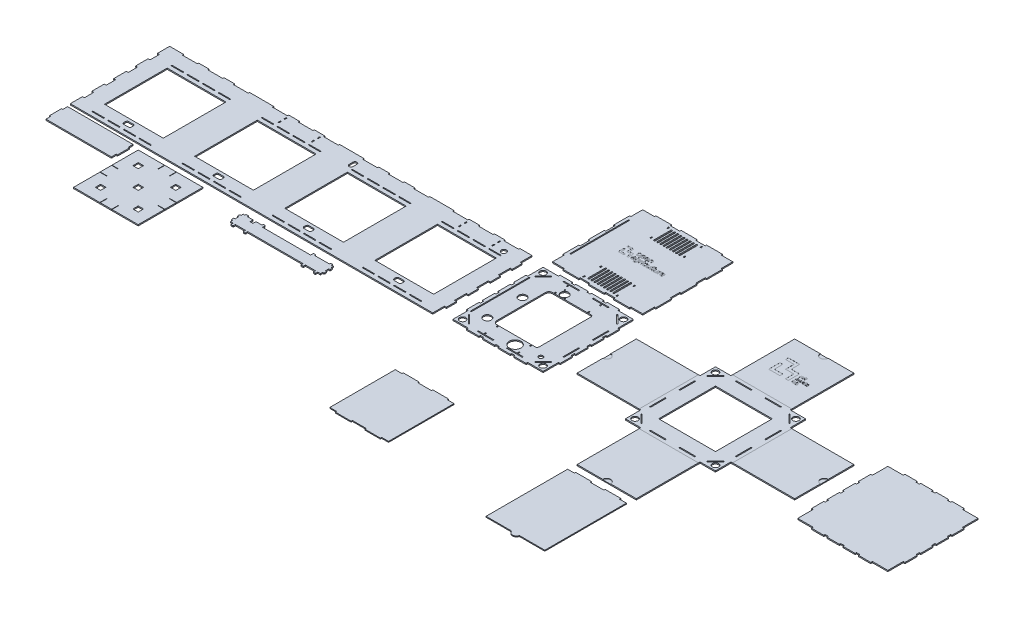
SolidWorks part; units mm, degrees
ref_plane "Front" through (0, 0, 0) normal (0, 0, 1) x (1, 0, 0)
ref_plane "Top" through (0, 0, 0) normal (0, 1, 0) x (1, 0, 0)
ref_plane "Right" through (0, 0, 0) normal (1, 0, 0) x (0, 0, -1)
sketch "Sketch1" plane through (0, 0, 0) normal (0, 1, 0) x (1, 0, 0)
  line L0 (0, 0) -> (438.15, 0) construction
  line L2 (-146.05, 160.9852) -> (-146.05, -160.9852) construction
  line L4 (146.05, 160.9852) -> (146.05, -160.9852) construction
  line L5 (-146.05, 160.9852) -> (146.05, -160.9852) construction
  line L6 (-146.05, -160.9852) -> (146.05, 160.9852) construction
  line L11 (146.05, 160.9852) -> (438.15, 160.9852)
  line L12 (146.05, 160.9852) -> (146.05, -160.9852) construction
  line L13 (146.05, -160.9852) -> (438.15, -160.9852)
  line L14 (438.15, 160.9852) -> (438.15, -160.9852) construction
  line L19 (-146.05, -160.9852) -> (-438.15, -160.9852)
  line L20 (-146.05, -160.9852) -> (-146.05, 160.9852) construction
  line L21 (-146.05, 160.9852) -> (-438.15, 160.9852)
  line L28 (146.05, -160.9852) -> (-146.05, -160.9852)
  line L34 (146.05, 160.9852) -> (-146.05, 160.9852)
  line L35 (-438.15, 160.9852) -> (-438.15, -160.9852) construction
  line L43 (-438.15, 160.9852) -> (-730.25, 160.9852)
  line L44 (-730.25, 160.9852) -> (-730.25, -160.9852) construction
  line L45 (-730.25, -160.9852) -> (-438.15, -160.9852)
  line L46 (438.15, 160.9852) -> (438.15, 122.9055)
  line L47 (438.15, 122.9055) -> (444.5, 122.9055)
  line L48 (444.5, 122.9055) -> (444.5, 90.0125)
  line L49 (444.5, 90.0125) -> (438.15, 90.0125)
  line L50 (438.15, 90.0125) -> (438.15, 51.9328)
  line L51 (438.15, 51.9328) -> (444.5, 51.9328)
  line L63 (444.5, 51.9328) -> (444.5, 19.0398)
  line L64 (444.5, 19.0398) -> (438.15, 19.0398)
  line L65 (438.15, 19.0398) -> (438.15, -19.0398)
  line L66 (438.15, -19.0398) -> (444.5, -19.0398)
  line L67 (444.5, -19.0398) -> (444.5, -51.9328)
  line L68 (444.5, -51.9328) -> (438.15, -51.9328)
  line L69 (438.15, -51.9328) -> (438.15, -90.0125)
  line L70 (438.15, -90.0125) -> (444.5, -90.0125)
  line L71 (444.5, -90.0125) -> (444.5, -122.9055)
  line L72 (444.5, -122.9055) -> (438.15, -122.9055)
  line L73 (438.15, -122.9055) -> (438.15, -160.9852)
  line L74 (-730.25, 160.9852) -> (-736.6, 160.9852)
  line L76 (-736.6, 121.699) -> (-730.25, 121.699)
  line L78 (-730.25, 91.219) -> (-736.6, 91.219)
  line L80 (-736.6, 50.7263) -> (-730.25, 50.7263)
  line L82 (-730.25, 20.2463) -> (-736.6, 20.2463)
  line L84 (-736.6, -20.2463) -> (-730.25, -20.2463)
  line L86 (-730.25, -50.7263) -> (-736.6, -50.7263)
  line L88 (-736.6, -91.219) -> (-730.25, -91.219)
  line L90 (-730.25, -121.699) -> (-736.6, -121.699)
  line L92 (-736.6, -160.9852) -> (-730.25, -160.9852)
  line L93 (444.5, 35.4863) -> (-730.25, 35.4863) construction
  line L94 (-730.25, 106.459) -> (444.5, 106.459) construction
  line L95 (-736.6, 160.9852) -> (-736.6, 121.699)
  line L96 (-736.6, 91.219) -> (-736.6, 50.7263)
  line L97 (-730.25, 121.699) -> (-730.25, 91.219)
  line L98 (-730.25, 50.7263) -> (-730.25, 20.2463)
  line L99 (-730.25, -20.2463) -> (-730.25, -50.7263)
  line L100 (-730.25, -91.219) -> (-730.25, -121.699)
  line L101 (-730.25, -106.459) -> (444.5, -106.459) construction
  line L102 (-730.25, -35.4863) -> (444.5, -35.4863) construction
  line L103 (-736.6, 20.2463) -> (-736.6, -20.2463)
  line L104 (-736.6, -50.7263) -> (-736.6, -91.219)
  line L105 (-736.6, -121.699) -> (-736.6, -160.9852)
  point P0 (0, 0)
  dimension "D1" = 292.1
  dimension "D4" = 32.893
  dimension "D5" = 30.48
  dimension "D2" = 321.9704
  dimension "D3" = 6.35
extrude "OVERALL DIMENSIONS AND MATERIAL THICKNESS" add sketch "Sketch1" along normal blind 3.81
sketch "WALL SCORE MARKS" plane through (0, 3.81, 0) normal (0, 1, 0) x (1, 0, 0)
  line L0 (-438.15, 160.9852) -> (-438.15, -160.9852) construction
  line L1 (-438.15, 160.9852) -> (-438.15, -160.9852)
  line L2 (-146.05, 160.9852) -> (-146.05, -160.9852) construction
  line L3 (-146.05, 160.9852) -> (-146.05, -160.9852)
  line L4 (146.05, 160.9852) -> (146.05, -160.9852) construction
  line L5 (146.05, 160.9852) -> (146.05, -160.9852)
sketch "Sketch5" plane through (0, 3.81, 0) normal (0, 1, 0) x (1, 0, 0)
  line L0 (-730.25, -20.2463) -> (-730.25, 20.2463) construction
  line L1 (-438.15, 0) -> (-730.25, 0) construction
  line L2 (-438.15, 160.9852) -> (-438.15, -160.9852) construction
  line L3 (-438.15, 0) -> (-146.05, 0) construction
  line L4 (-146.05, 160.9852) -> (-146.05, -160.9852) construction
  line L5 (-146.05, 0) -> (146.05, 0) construction
  line L6 (146.05, 160.9852) -> (146.05, -160.9852) construction
  line L7 (146.05, 0) -> (438.15, 0) construction
  line L8 (438.15, -19.0398) -> (438.15, 19.0398) construction
  line L9 (-584.2, -5.6134) -> (-584.2, -160.9852) construction
  line L10 (-736.6, -160.9852) -> (438.15, -160.9852) construction
  line L11 (-292.1, -5.6134) -> (-292.1, -160.9852) construction
  line L12 (0, -5.6134) -> (0, -160.9852) construction
  line L13 (292.1, -5.6134) -> (292.1, -160.9852) construction
  line L14 (-488.95, -148.2852) -> (-488.95, -160.9852) construction
  line L15 (-679.45, -145.3134) -> (-488.95, -145.3134)
  line L16 (-679.45, -145.3134) -> (-679.45, -148.2852)
  line L17 (-679.45, -148.2852) -> (-488.95, -148.2852)
  line L18 (-488.95, -145.3134) -> (-488.95, -148.2852)
  line L19 (-679.45, -145.3134) -> (-488.95, -148.2852) construction
  line L20 (-679.45, -148.2852) -> (-488.95, -145.3134) construction
  line L21 (-387.35, -145.3134) -> (-196.85, -145.3134)
  line L22 (-387.35, -145.3134) -> (-387.35, -148.2852)
  line L23 (-387.35, -148.2852) -> (-196.85, -148.2852)
  line L24 (-196.85, -145.3134) -> (-196.85, -148.2852)
  line L25 (-387.35, -145.3134) -> (-196.85, -148.2852) construction
  line L26 (-387.35, -148.2852) -> (-196.85, -145.3134) construction
  line L27 (-95.25, -148.2852) -> (95.25, -148.2852)
  line L28 (-95.25, -148.2852) -> (-95.25, -145.3134)
  line L29 (-95.25, -145.3134) -> (95.25, -145.3134)
  line L30 (95.25, -148.2852) -> (95.25, -145.3134)
  line L31 (-95.25, -148.2852) -> (95.25, -145.3134) construction
  line L32 (-95.25, -145.3134) -> (95.25, -148.2852) construction
  line L33 (196.85, -148.2852) -> (387.35, -148.2852)
  line L34 (196.85, -148.2852) -> (196.85, -145.3134)
  line L35 (196.85, -145.3134) -> (387.35, -145.3134)
  line L36 (387.35, -148.2852) -> (387.35, -145.3134)
  line L37 (196.85, -148.2852) -> (387.35, -145.3134) construction
  line L38 (196.85, -145.3134) -> (387.35, -148.2852) construction
  line L39 (444.5, 90.0125) -> (444.5, 122.9055) construction
  line L47 (-584.2, -5.6134) -> (-584.2, 110.1725) construction
  line L64 (-292.1, -5.6134) -> (-292.1, 110.1725) construction
  line L65 (-679.45, 95.9866) -> (-488.95, 95.9866)
  line L66 (-679.45, 95.9866) -> (-679.45, -107.2134)
  line L67 (-679.45, -107.2134) -> (-488.95, -107.2134)
  line L68 (-488.95, 95.9866) -> (-488.95, -107.2134)
  line L69 (-679.45, 95.9866) -> (-488.95, -107.2134) construction
  line L70 (-679.45, -107.2134) -> (-488.95, 95.9866) construction
  line L71 (-387.35, 95.9866) -> (-196.85, 95.9866)
  line L72 (-387.35, 95.9866) -> (-387.35, -107.2134)
  line L73 (-387.35, -107.2134) -> (-196.85, -107.2134)
  line L74 (-196.85, 95.9866) -> (-196.85, -107.2134)
  line L75 (-387.35, 95.9866) -> (-196.85, -107.2134) construction
  line L76 (-387.35, -107.2134) -> (-196.85, 95.9866) construction
  line L77 (-95.25, 95.9866) -> (95.25, 95.9866)
  line L78 (-95.25, 95.9866) -> (-95.25, -107.2134)
  line L79 (-95.25, -107.2134) -> (95.25, -107.2134)
  line L80 (95.25, 95.9866) -> (95.25, -107.2134)
  line L81 (-95.25, 95.9866) -> (95.25, -107.2134) construction
  line L82 (-95.25, -107.2134) -> (95.25, 95.9866) construction
  line L83 (196.85, 95.9866) -> (387.35, 95.9866)
  line L84 (196.85, 95.9866) -> (196.85, -107.2134)
  line L85 (196.85, -107.2134) -> (387.35, -107.2134)
  line L86 (387.35, 95.9866) -> (387.35, -107.2134)
  line L87 (196.85, 95.9866) -> (387.35, -107.2134) construction
  line L88 (196.85, -107.2134) -> (387.35, 95.9866) construction
  line L89 (0, -5.6134) -> (0, 110.1725) construction
  line L90 (292.1, -5.6134) -> (292.1, 110.1725) construction
  line L91 (-387.35, -107.2134) -> (-387.35, -145.3134) construction
  line L92 (-679.45, 111.6584) -> (-488.95, 111.6584)
  line L93 (-679.45, 111.6584) -> (-679.45, 108.6866)
  line L94 (-679.45, 108.6866) -> (-488.95, 108.6866)
  line L95 (-488.95, 111.6584) -> (-488.95, 108.6866)
  line L96 (-679.45, 111.6584) -> (-488.95, 108.6866) construction
  line L97 (-679.45, 108.6866) -> (-488.95, 111.6584) construction
  line L98 (-387.35, 111.6584) -> (-196.85, 111.6584)
  line L99 (-387.35, 111.6584) -> (-387.35, 108.6866)
  line L100 (-387.35, 108.6866) -> (-196.85, 108.6866)
  line L101 (-196.85, 111.6584) -> (-196.85, 108.6866)
  line L102 (-387.35, 111.6584) -> (-196.85, 108.6866) construction
  line L103 (-387.35, 108.6866) -> (-196.85, 111.6584) construction
  line L104 (-95.25, 111.6584) -> (95.25, 111.6584)
  line L105 (-95.25, 111.6584) -> (-95.25, 108.6866)
  line L106 (-95.25, 108.6866) -> (95.25, 108.6866)
  line L107 (95.25, 111.6584) -> (95.25, 108.6866)
  line L108 (-95.25, 111.6584) -> (95.25, 108.6866) construction
  line L109 (-95.25, 108.6866) -> (95.25, 111.6584) construction
  line L110 (196.85, 111.6584) -> (387.35, 111.6584)
  line L111 (196.85, 111.6584) -> (196.85, 108.6866)
  line L112 (196.85, 108.6866) -> (387.35, 108.6866)
  line L113 (387.35, 111.6584) -> (387.35, 108.6866)
  line L114 (196.85, 111.6584) -> (387.35, 108.6866) construction
  line L115 (196.85, 108.6866) -> (387.35, 111.6584) construction
  line L116 (-196.85, -107.2134) -> (-196.85, -145.3134) construction
  line L117 (-196.85, -126.2634) -> (-387.35, -126.2634) construction
  line L118 (-7.62, -132.6134) -> (7.62, -132.6134)
  line L119 (-299.72, -116.7384) -> (-284.48, -116.7384)
  line L120 (-304.8, -121.8184) -> (-304.8, -127.5334)
  line L121 (-299.72, -132.6134) -> (-284.48, -132.6134)
  line L122 (-279.4, -121.8184) -> (-279.4, -127.5334)
  line L123 (-304.8, -116.7384) -> (-279.4, -132.6134) construction
  line L124 (-304.8, -132.6134) -> (-279.4, -116.7384) construction
  line L125 (-12.7, -121.8184) -> (-12.7, -127.5334)
  line L126 (-7.62, -116.7384) -> (7.62, -116.7384)
  line L127 (12.7, -121.8184) -> (12.7, -127.5334)
  line L128 (284.48, -132.6134) -> (299.72, -132.6134)
  line L129 (279.4, -121.8184) -> (279.4, -127.5334)
  line L130 (284.48, -116.7384) -> (299.72, -116.7384)
  line L131 (304.8, -121.8184) -> (304.8, -127.5334)
  line L132 (-596.9, -121.8184) -> (-596.9, -127.5334)
  line L133 (-591.82, -116.7384) -> (-576.58, -116.7384)
  line L134 (-571.5, -121.8184) -> (-571.5, -127.5334)
  line L135 (-591.82, -132.6134) -> (-576.58, -132.6134)
  line L136 (438.15, 160.9852) -> (-736.6, 160.9852) construction
  line L137 (-107.95, 133.2484) -> (-107.95, 120.5484) construction
  line L138 (-101.6, 133.2484) -> (-101.6, 120.5484)
  line L139 (-114.3, 133.2484) -> (-114.3, 120.5484)
  line L142 (-107.95, 126.8984) -> (381, 126.8984) construction
  arc A0 (-284.48, -116.7384) -> (-279.4, -121.8184) centre (-284.48, -121.8184) cw
  arc A1 (-279.4, -127.5334) -> (-284.48, -132.6134) centre (-284.48, -127.5334) cw
  arc A2 (-299.72, -132.6134) -> (-304.8, -127.5334) centre (-299.72, -127.5334) cw
  arc A3 (-304.8, -121.8184) -> (-299.72, -116.7384) centre (-299.72, -121.8184) cw
  arc A4 (-7.62, -132.6134) -> (-12.7, -127.5334) centre (-7.62, -127.5334) cw
  arc A5 (-12.7, -121.8184) -> (-7.62, -116.7384) centre (-7.62, -121.8184) cw
  arc A6 (7.62, -116.7384) -> (12.7, -121.8184) centre (7.62, -121.8184) cw
  arc A7 (12.7, -127.5334) -> (7.62, -132.6134) centre (7.62, -127.5334) cw
  arc A8 (284.48, -132.6134) -> (279.4, -127.5334) centre (284.48, -127.5334) cw
  arc A9 (279.4, -121.8184) -> (284.48, -116.7384) centre (284.48, -121.8184) cw
  arc A10 (299.72, -116.7384) -> (304.8, -121.8184) centre (299.72, -121.8184) cw
  arc A11 (304.8, -127.5334) -> (299.72, -132.6134) centre (299.72, -127.5334) cw
  arc A12 (-596.9, -121.8184) -> (-591.82, -116.7384) centre (-591.82, -121.8184) cw
  arc A13 (-591.82, -132.6134) -> (-596.9, -127.5334) centre (-591.82, -127.5334) cw
  arc A14 (-576.58, -116.7384) -> (-571.5, -121.8184) centre (-576.58, -121.8184) cw
  arc A15 (-571.5, -127.5334) -> (-576.58, -132.6134) centre (-576.58, -127.5334) cw
  arc A16 (-101.6, 133.2484) -> (-114.3, 133.2484) centre (-107.95, 133.2484) ccw
  arc A17 (-114.3, 120.5484) -> (-101.6, 120.5484) centre (-107.95, 120.5484) ccw
  circle A18 centre (381, 126.8984) radius 8.255
  point P27 (-584.2, -146.7993)
  point P32 (-292.1, -146.7993)
  point P37 (0, -146.7993)
  point P42 (292.1, -146.7993)
  point P106 (-292.1, -124.6759)
  point P148 (0, -132.6134)
  point P161 (-584.2, -132.6134)
  point P165 (-107.95, 126.8984)
  point P176 (-584.2, 0)
  point P178 (-292.1, 0)
  point P179 (0, 0)
  point P180 (292.1, 0)
  dimension "D9" = 5.08
  dimension "D17" = 16.51
  dimension "D1" = 12.7
  dimension "D3" = 190.5
  dimension "D4" = 203.2
  dimension "D5" = 12.7
  dimension "D6" = 12.7
  dimension "D8" = 25.4
  dimension "D13" = 12.7
  dimension "D14" = 25.4
  dimension "D16" = 2.54
  dimension "D19" = 190.5
  dimension "D20" = 38.1
  dimension "D15" = 38.1
  dimension "D18" = 63.5
  dimension "D7" = 15.875
  dimension "D10" = 3
  dimension "D11" = 2
extrude "WINDOWS AND HORIZONTAL SLATS" cut sketch "Sketch5" against normal through all
sketch "Sketch6" plane through (0, 0, 0) normal (0, 1, 0) x (1, 0, 0)
  line L0 (0, 0) -> (635, 0) construction
  line L1 (635, 0) -> (635, 148.717) construction
  line L2 (488.95, 146.05) -> (781.05, 146.05) construction
  line L3 (488.95, 146.05) -> (488.95, -146.05) construction
  line L4 (488.95, -146.05) -> (781.05, -146.05) construction
  line L5 (781.05, 146.05) -> (781.05, -146.05) construction
  line L6 (488.95, 146.05) -> (781.05, -146.05) construction
  line L7 (488.95, -146.05) -> (781.05, 146.05) construction
  line L8 (635, 0) -> (783.717, 0) construction
  line L9 (635, 0) -> (635, -148.717) construction
  line L10 (488.95, 96.139) -> (488.95, 146.05)
  line L11 (538.861, 151.384) -> (731.139, 151.384)
  line L12 (538.861, 151.384) -> (538.861, 146.05)
  line L13 (538.861, 146.05) -> (731.139, 146.05) construction
  line L14 (731.139, 151.384) -> (731.139, 146.05)
  line L15 (538.861, 151.384) -> (731.139, 146.05) construction
  line L16 (538.861, 146.05) -> (731.139, 151.384) construction
  line L17 (786.384, -96.139) -> (781.05, -96.139)
  line L18 (786.384, -96.139) -> (786.384, 96.139)
  line L19 (786.384, 96.139) -> (781.05, 96.139)
  line L20 (781.05, -96.139) -> (781.05, 96.139) construction
  line L21 (786.384, -96.139) -> (781.05, 96.139) construction
  line L22 (786.384, 96.139) -> (781.05, -96.139) construction
  line L23 (538.861, -151.384) -> (731.139, -151.384)
  line L24 (538.861, -151.384) -> (538.861, -146.05)
  line L25 (538.861, -146.05) -> (731.139, -146.05) construction
  line L26 (731.139, -151.384) -> (731.139, -146.05)
  line L27 (538.861, -151.384) -> (731.139, -146.05) construction
  line L28 (538.861, -146.05) -> (731.139, -151.384) construction
  line L29 (483.616, 96.139) -> (488.95, 96.139)
  line L30 (483.616, 96.139) -> (483.616, -96.139)
  line L31 (483.616, -96.139) -> (488.95, -96.139)
  line L32 (488.95, 96.139) -> (488.95, -96.139) construction
  line L33 (483.616, 96.139) -> (488.95, -96.139) construction
  line L34 (483.616, -96.139) -> (488.95, 96.139) construction
  line L35 (488.95, 146.05) -> (538.861, 146.05)
  line L36 (731.139, 146.05) -> (781.05, 146.05)
  line L37 (781.05, 146.05) -> (781.05, 96.139)
  line L38 (781.05, -96.139) -> (781.05, -146.05)
  line L39 (781.05, -146.05) -> (731.139, -146.05)
  line L40 (538.861, -146.05) -> (488.95, -146.05)
  line L41 (488.95, -146.05) -> (488.95, -96.139)
  line L42 (1042.416, 96.139) -> (1042.416, -96.139)
  line L43 (1042.416, 96.139) -> (1047.75, 96.139)
  line L44 (1047.75, 96.139) -> (1047.75, 146.05)
  line L45 (1047.75, 146.05) -> (1097.661, 146.05)
  line L46 (1097.661, 151.384) -> (1097.661, 146.05)
  line L47 (1097.661, 151.384) -> (1289.939, 151.384)
  line L48 (1289.939, 151.384) -> (1289.939, 146.05)
  line L49 (1289.939, 146.05) -> (1339.85, 146.05)
  line L50 (1339.85, 146.05) -> (1339.85, 96.139)
  line L51 (1345.184, 96.139) -> (1339.85, 96.139)
  line L52 (1345.184, -96.139) -> (1345.184, 96.139)
  line L53 (1345.184, -96.139) -> (1339.85, -96.139)
  line L54 (1339.85, -96.139) -> (1339.85, -146.05)
  line L55 (1339.85, -146.05) -> (1289.939, -146.05)
  line L56 (1289.939, -151.384) -> (1289.939, -146.05)
  line L57 (1097.661, -151.384) -> (1289.939, -151.384)
  line L58 (1097.661, -151.384) -> (1097.661, -146.05)
  line L59 (1097.661, -146.05) -> (1047.75, -146.05)
  line L60 (1047.75, -146.05) -> (1047.75, -96.139)
  line L61 (1042.416, -96.139) -> (1047.75, -96.139)
  line L62 (1047.75, 146.05) -> (1339.85, -146.05) construction
  line L63 (1601.216, 96.139) -> (1601.216, -96.139)
  line L64 (1601.216, 96.139) -> (1606.55, 96.139)
  line L65 (1606.55, 96.139) -> (1606.55, 146.05)
  line L66 (1606.55, 146.05) -> (1656.461, 146.05)
  line L67 (1656.461, 151.384) -> (1656.461, 146.05)
  line L68 (1656.461, 151.384) -> (1848.739, 151.384)
  line L69 (1848.739, 151.384) -> (1848.739, 146.05)
  line L70 (1848.739, 146.05) -> (1898.65, 146.05)
  line L71 (1898.65, 146.05) -> (1898.65, 96.139)
  line L72 (1903.984, 96.139) -> (1898.65, 96.139)
  line L73 (1903.984, -96.139) -> (1903.984, 96.139)
  line L74 (1903.984, -96.139) -> (1898.65, -96.139)
  line L75 (1898.65, -96.139) -> (1898.65, -146.05)
  line L76 (1898.65, -146.05) -> (1848.739, -146.05)
  line L77 (1848.739, -151.384) -> (1848.739, -146.05)
  line L78 (1656.461, -151.384) -> (1848.739, -151.384)
  line L79 (1656.461, -151.384) -> (1656.461, -146.05)
  line L80 (1656.461, -146.05) -> (1606.55, -146.05)
  line L81 (1606.55, -146.05) -> (1606.55, -96.139)
  line L82 (1601.216, -96.139) -> (1606.55, -96.139)
  line L83 (1752.6, 151.384) -> (1752.6, -151.384) construction
  line L84 (1101.725, 92.075) -> (1285.875, 92.075)
  line L85 (1101.725, 92.075) -> (1101.725, -92.075)
  line L86 (1101.725, -92.075) -> (1285.875, -92.075)
  line L87 (1285.875, 92.075) -> (1285.875, -92.075)
  line L88 (1101.725, 92.075) -> (1285.875, -92.075) construction
  line L89 (1101.725, -92.075) -> (1285.875, 92.075) construction
  point P22 (486.283, 0)
  point P67 (1193.8, 0)
  dimension "D1" = 292.1
  dimension "D2" = 292.1
  dimension "D4" = 192.278
  dimension "D5" = 635
  dimension "D8" = 184.15
  dimension "D9" = 256.032
  dimension "D7" = 558.8
extrude "HORIZONTAL PLATFORMS" add sketch "Sketch6" along normal up to surface (3.81 mm away) separate body up to face at (0, 3.81, 124.6759)
sketch "Sketch7" plane through (0, 0, 0) normal (0, 1, 0) x (1, 0, 0)
  line L0 (-679.45, 108.6866) -> (-679.45, -103.378) construction
  line L1 (-732.536, -173.6852) -> (-520.4714, -173.6852)
  line L2 (-732.536, -173.6852) -> (-732.536, -189.0522)
  line L3 (-732.536, -243.7892) -> (-520.4714, -243.7892)
  line L4 (-520.4714, -173.6852) -> (-520.4714, -189.0522)
  line L5 (-732.536, -173.6852) -> (-520.4714, -243.7892) construction
  line L6 (-732.536, -243.7892) -> (-520.4714, -173.6852) construction
  line L7 (-679.45, 95.9866) -> (-679.45, -107.2134) construction
  line L8 (-679.45, -103.378) -> (-679.45, -107.2134) construction
  line L9 (488.95, -96.139) -> (488.95, -146.05) construction
  line L10 (488.95, -146.05) -> (538.861, -146.05) construction
  line L12 (-732.536, -189.0522) -> (-736.6, -189.0522)
  line L13 (502.5904, -105.4689) -> (529.5311, -132.4096) construction
  line L14 (502.5904, -105.4689) -> (500.4351, -107.6241) construction
  line L15 (500.4351, -107.6241) -> (527.3759, -134.5649) construction
  line L16 (529.5311, -132.4096) -> (527.3759, -134.5649) construction
  line L17 (502.5904, -105.4689) -> (527.3759, -134.5649) construction
  line L18 (500.4351, -107.6241) -> (529.5311, -132.4096) construction
  line L19 (-736.6, -189.0522) -> (-736.6, -228.4222)
  line L20 (-736.6, -228.4222) -> (-732.536, -228.4222)
  line L21 (488.95, -96.139) -> (538.861, -146.05) construction
  line L22 (514.9831, -120.0169) -> (513.9055, -121.0945) construction
  line L23 (-732.536, -228.4222) -> (-732.536, -243.7892)
  line L24 (-520.4714, -189.0522) -> (-516.4074, -189.0522)
  line L25 (-516.4074, -189.0522) -> (-516.4074, -228.4222)
  line L26 (-516.4074, -228.4222) -> (-520.4714, -228.4222)
  line L27 (-520.4714, -228.4222) -> (-520.4714, -243.7892)
  line L28 (-736.6, -160.9852) -> (438.15, -160.9852) construction
  line L29 (-736.6, -121.699) -> (-736.6, -160.9852) construction
  point P0 (-626.5037, -208.7372)
  point P14 (514.9831, -120.0169)
  dimension "D5" = 38.1
  dimension "D7" = 12.7
  dimension "D4" = 39.37
  dimension "D2" = 3.8354
  dimension "D1" = 70.104
extrude "CORNER SUPPORT" add sketch "Sketch7" along normal up to surface (3.81 mm away) separate body up to face at (0, 3.81, 124.6759)
sketch "Sketch8" plane through (0, 3.81, 0) normal (0, 1, 0) x (1, 0, 0)
  line L0 (500.4351, -107.6241) -> (527.3759, -134.5649) construction
  line L1 (529.5311, -132.4096) -> (527.3759, -134.5649) construction
  line L2 (502.5904, -105.4689) -> (529.5311, -132.4096) construction
  line L3 (502.5904, -105.4689) -> (500.4351, -107.6241) construction
  line L4 (500.4351, -107.6241) -> (527.3759, -134.5649)
  line L5 (529.5311, -132.4096) -> (527.3759, -134.5649)
  line L6 (502.5904, -105.4689) -> (529.5311, -132.4096)
  line L7 (502.5904, -105.4689) -> (500.4351, -107.6241)
  line L8 (488.95, 146.05) -> (781.05, -146.05) construction
  line L9 (529.5311, 132.4096) -> (502.5904, 105.4689)
  line L10 (529.5311, 132.4096) -> (527.3759, 134.5649)
  line L11 (527.3759, 134.5649) -> (500.4351, 107.6241)
  line L12 (502.5904, 105.4689) -> (500.4351, 107.6241)
  line L13 (767.4096, 105.4689) -> (740.4689, 132.4096)
  line L14 (767.4096, 105.4689) -> (769.5649, 107.6241)
  line L15 (769.5649, 107.6241) -> (742.6241, 134.5649)
  line L16 (740.4689, 132.4096) -> (742.6241, 134.5649)
  line L17 (740.4689, -132.4096) -> (767.4096, -105.4689)
  line L18 (740.4689, -132.4096) -> (742.6241, -134.5649)
  line L19 (742.6241, -134.5649) -> (769.5649, -107.6241)
  line L20 (767.4096, -105.4689) -> (769.5649, -107.6241)
  line L21 (1047.75, -96.139) -> (1097.661, -146.05) construction
  line L22 (1059.2351, -107.6241) -> (1061.3904, -105.4689)
  line L23 (1061.3904, -105.4689) -> (1088.3311, -132.4096)
  line L24 (1088.3311, -132.4096) -> (1086.1759, -134.5649)
  line L25 (1072.7055, -121.0945) -> (1074.8608, -118.9392) construction
  line L26 (1059.2351, -107.6241) -> (1086.1759, -134.5649)
  line L27 (1047.75, 146.05) -> (1339.85, -146.05) construction
  line L28 (1061.3904, 105.4689) -> (1059.2351, 107.6241)
  line L29 (1086.1759, 134.5649) -> (1059.2351, 107.6241)
  line L30 (1086.1759, 134.5649) -> (1088.3311, 132.4096)
  line L31 (1088.3311, 132.4096) -> (1061.3904, 105.4689)
  line L32 (1299.2689, 132.4096) -> (1301.4241, 134.5649)
  line L33 (1328.3649, 107.6241) -> (1301.4241, 134.5649)
  line L34 (1328.3649, 107.6241) -> (1326.2096, 105.4689)
  line L35 (1326.2096, 105.4689) -> (1299.2689, 132.4096)
  line L36 (1326.2096, -105.4689) -> (1328.3649, -107.6241)
  line L37 (1301.4241, -134.5649) -> (1328.3649, -107.6241)
  line L38 (1301.4241, -134.5649) -> (1299.2689, -132.4096)
  line L39 (1299.2689, -132.4096) -> (1326.2096, -105.4689)
  circle A0 centre (635, 0) radius 20.7898 construction
  circle A1 centre (635, 0) radius 20.7898 construction
  circle A2 centre (635, 0) radius 20.7898 construction
  circle A3 centre (635, 0) radius 20.7898 construction
  circle A4 centre (1193.8, 0) radius 130.2137 construction
  circle A5 centre (1063.4654, 130.3346) radius 10
  circle A9 centre (1324.1346, 130.3346) radius 10
  circle A10 centre (1324.1346, -130.3346) radius 10
  circle A11 centre (1063.4654, -130.3346) radius 10
  circle A12 centre (504.6654, 130.3346) radius 10
  circle A13 centre (765.3346, 130.3346) radius 10
  circle A14 centre (765.3346, -130.3346) radius 10
  circle A15 centre (504.6654, -130.3346) radius 10
  point P28 (635, 0)
  point P58 (1193.8, 0)
  point P67 (1193.8, 0)
  point P76 (635, 0)
  dimension "D3" = 20
  dimension "D4" = 22.225
  dimension "D6" = 22.225
  dimension "D1" = 4
  dimension "D2" = 4
  dimension "D5" = 4
  dimension "D7" = 4
extrude "ACCESS HOLES" cut sketch "Sketch8" against normal through all
sketch "Sketch9" plane through (0, 0, 0) normal (0, 1, 0) x (1, 0, 0)
  line L0 (-736.6, -160.9852) -> (438.15, -160.9852) construction
  line L1 (-496.4074, -180.9852) -> (-286.8574, -180.9852)
  line L2 (-496.4074, -180.9852) -> (-496.4074, -390.5352)
  line L3 (-496.4074, -390.5352) -> (-286.8574, -390.5352)
  line L4 (-286.8574, -180.9852) -> (-286.8574, -390.5352)
  line L5 (-496.4074, -180.9852) -> (-286.8574, -390.5352) construction
  line L6 (-496.4074, -390.5352) -> (-286.8574, -180.9852) construction
  line L7 (-400.2684, -277.1242) -> (-382.9964, -277.1242)
  line L8 (-400.2684, -277.1242) -> (-400.2684, -294.3962)
  line L9 (-400.2684, -294.3962) -> (-382.9964, -294.3962)
  line L10 (-382.9964, -277.1242) -> (-382.9964, -294.3962)
  line L11 (-400.2684, -277.1242) -> (-382.9964, -294.3962) construction
  line L12 (-400.2684, -294.3962) -> (-382.9964, -277.1242) construction
  line L13 (-452.5311, -224.8615) -> (-330.7337, -224.8615) construction
  line L14 (-452.5311, -224.8615) -> (-452.5311, -346.6589) construction
  line L15 (-452.5311, -346.6589) -> (-330.7337, -346.6589) construction
  line L16 (-330.7337, -224.8615) -> (-330.7337, -346.6589) construction
  line L17 (-452.5311, -224.8615) -> (-330.7337, -346.6589) construction
  line L18 (-452.5311, -346.6589) -> (-330.7337, -224.8615) construction
  line L19 (-461.1671, -216.2255) -> (-443.8951, -216.2255)
  line L20 (-461.1671, -216.2255) -> (-461.1671, -233.4975)
  line L21 (-461.1671, -233.4975) -> (-443.8951, -233.4975)
  line L22 (-443.8951, -216.2255) -> (-443.8951, -233.4975)
  line L23 (-461.1671, -216.2255) -> (-443.8951, -233.4975) construction
  line L24 (-461.1671, -233.4975) -> (-443.8951, -216.2255) construction
  line L25 (-461.1671, -338.0229) -> (-443.8951, -338.0229)
  line L26 (-461.1671, -338.0229) -> (-461.1671, -355.2949)
  line L27 (-461.1671, -355.2949) -> (-443.8951, -355.2949)
  line L28 (-443.8951, -338.0229) -> (-443.8951, -355.2949)
  line L29 (-461.1671, -338.0229) -> (-443.8951, -355.2949) construction
  line L30 (-461.1671, -355.2949) -> (-443.8951, -338.0229) construction
  line L31 (-322.0977, -338.0229) -> (-339.3697, -338.0229)
  line L32 (-322.0977, -338.0229) -> (-322.0977, -355.2949)
  line L33 (-322.0977, -355.2949) -> (-339.3697, -355.2949)
  line L34 (-339.3697, -338.0229) -> (-339.3697, -355.2949)
  line L35 (-322.0977, -338.0229) -> (-339.3697, -355.2949) construction
  line L36 (-322.0977, -355.2949) -> (-339.3697, -338.0229) construction
  line L37 (-339.3697, -216.2255) -> (-322.0977, -216.2255)
  line L38 (-339.3697, -216.2255) -> (-339.3697, -233.4975)
  line L39 (-339.3697, -233.4975) -> (-322.0977, -233.4975)
  line L40 (-322.0977, -216.2255) -> (-322.0977, -233.4975)
  line L41 (-339.3697, -216.2255) -> (-322.0977, -233.4975) construction
  line L42 (-339.3697, -233.4975) -> (-322.0977, -216.2255) construction
  line L43 (-516.4074, -228.4222) -> (-516.4074, -189.0522) construction
  point P0 (-391.6324, -285.7602)
  point P5 (-391.6324, -285.7602)
  point P12 (-391.6324, -285.7602)
  dimension "D1" = 209.55
  dimension "D2" = 209.55
  dimension "D3" = 17.272
  dimension "D4" = 17.272
  dimension "D5" = 20
  dimension "D6" = 20
  dimension "D7" = 121.7975
extrude "HORTICUBE HOUSING" add sketch "Sketch9" along normal up to surface (3.81 mm away) separate body up to face at (0, 3.81, 124.6759)
sketch "Sketch10" [suppressed] plane through (0, 3.81, 0) normal (0, 1, 0) x (1, 0, 0)
  line L8 (-679.45, -103.2764) -> (-488.95, -103.2764)
  line L9 (-584.2, -103.2764) -> (-584.2, -107.2134) construction
  line L14 (-679.45, 95.9866) -> (-679.45, -107.2134) construction
  line L15 (-488.95, -107.2134) -> (-488.95, 95.9866) construction
  line L16 (-679.45, -107.2134) -> (-488.95, -107.2134) construction
  line L17 (-387.35, -103.2764) -> (-196.85, -103.2764)
  line L18 (-387.35, 95.9866) -> (-387.35, -107.2134) construction
  line L19 (-196.85, -107.2134) -> (-196.85, 95.9866) construction
  line L20 (-95.25, -103.2764) -> (95.25, -103.2764)
  line L21 (-95.25, 95.9866) -> (-95.25, -107.2134) construction
  line L22 (95.25, -107.2134) -> (95.25, 95.9866) construction
  line L23 (196.85, -103.2764) -> (387.35, -103.2764)
  line L24 (196.85, 95.9866) -> (196.85, -107.2134) construction
  line L25 (387.35, -107.2134) -> (387.35, 95.9866) construction
  dimension "D2" = 3.937
sketch "Sketch11" plane through (0, 3.81, 0) normal (0, 1, 0) x (1, 0, 0)
  line L0 (488.95, 146.05) -> (781.05, -146.05) construction
  line L2 (553.0739, -86.2323) -> (527.6989, -86.2323) construction
  line L18 (731.139, -146.05) -> (781.05, -146.05) construction
  line L19 (781.05, -146.05) -> (781.05, -96.139) construction
  line L130 (699.863, 90.3227) -> (574.863, 90.3227)
  line L131 (563.5613, 79.021) -> (563.5613, -78.979)
  line L132 (574.863, -90.2808) -> (699.863, -90.2808)
  line L137 (706.1648, -83.979) -> (706.1648, 84.021)
  circle A0 centre (540.385, 28.067) radius 12.6875
  circle A1 centre (600.5844, 104.3237) radius 12.6875
  circle A2 centre (612.3808, 93.3292) radius 1.7055
  circle A3 centre (588.3905, 117.3172) radius 1.7055
  circle A6 centre (660.6231, -116.4583) radius 19.0375
  arc A7 (706.1648, 84.021) -> (699.863, 90.3227) centre (699.863, 84.021) ccw
  arc A8 (699.863, -90.2808) -> (706.1648, -83.979) centre (699.863, -83.979) ccw
  arc A9 (563.5613, -78.979) -> (574.863, -90.2808) centre (574.863, -78.979) ccw
  arc A10 (574.863, 90.3227) -> (563.5613, 79.021) centre (574.863, 79.021) ccw
  circle A14 centre (540.385, 28.067) radius 12.6875 construction
  circle A15 centre (600.5844, 104.3237) radius 12.6875 construction
  circle A16 centre (612.3808, 93.3292) radius 1.7055 construction
  circle A17 centre (588.3905, 117.3172) radius 1.7055 construction
  circle A24 centre (737.0572, -109.22) radius 6.7474
  circle A105 centre (660.6231, -116.4583) radius 19.0375 construction
  arc A123 (527.6989, -86.2323) -> (553.0739, -86.2323) centre (540.3864, -86.2323) ccw
  arc A127 (553.0739, -86.2323) -> (527.6989, -86.2323) centre (540.3864, -86.2323) ccw
  arc A128 (706.1648, 84.021) -> (699.863, 90.3227) centre (699.863, 84.021) ccw construction
  arc A129 (574.863, 90.3227) -> (563.5613, 79.021) centre (574.863, 79.021) ccw construction
  arc A130 (563.5613, -78.979) -> (574.863, -90.2808) centre (574.863, -78.979) ccw construction
  arc A166 (699.863, -90.2808) -> (706.1648, -83.979) centre (699.863, -83.979) ccw construction
  dimension "D1" = 13.4948
  dimension "D2" = 36.83
  dimension "D3" = 43.9928
extrude "PCB FEATURES" cut sketch "Sketch11" against normal through all
sketch "Sketch12" plane through (0, 3.81, 0) normal (0, 1, 0) x (1, 0, 0)
  line L0 (483.616, 0) -> (563.5613, 0.021) construction
  line L1 (483.616, 96.139) -> (483.616, -96.139) construction
  line L2 (563.5613, 79.021) -> (563.5613, -78.979) construction
  line L3 (495.9096, 95.2532) -> (495.9096, 0.0032) construction
  line L4 (494.2586, 95.2532) -> (497.5606, 95.2532) construction
  line L5 (494.2586, 95.2532) -> (494.2586, -95.2468) construction
  line L6 (494.2586, -95.2468) -> (497.5606, -95.2468) construction
  line L7 (497.5606, 95.2532) -> (497.5606, -95.2468) construction
  line L8 (494.2586, 95.2532) -> (497.5606, -95.2468) construction
  line L9 (494.2586, -95.2468) -> (497.5606, 95.2532) construction
  line L10 (495.9096, 0.0032) -> (495.9096, -95.2468) construction
  line L11 (488.95, 146.05) -> (781.05, -146.05) construction
  line L12 (494.2586, -22.2218) -> (497.5606, -22.2218)
  line L13 (494.2586, -22.2218) -> (494.2586, -73.0218)
  line L14 (494.2586, -73.0218) -> (497.5606, -73.0218)
  line L15 (497.5606, -22.2218) -> (497.5606, -73.0218)
  line L16 (494.2586, -22.2218) -> (497.5606, -73.0218) construction
  line L17 (494.2586, -73.0218) -> (497.5606, -22.2218) construction
  line L18 (494.2586, 73.0282) -> (497.5606, 73.0282)
  line L19 (494.2586, 73.0282) -> (494.2586, 22.2282)
  line L20 (494.2586, 22.2282) -> (497.5606, 22.2282)
  line L21 (497.5606, 73.0282) -> (497.5606, 22.2282)
  line L22 (494.2586, 73.0282) -> (497.5606, 22.2282) construction
  line L23 (494.2586, 22.2282) -> (497.5606, 73.0282) construction
  line L24 (708.0282, 140.7414) -> (657.2282, 140.7414)
  line L25 (612.7782, 140.7414) -> (612.7782, 137.4394)
  line L26 (612.7782, 140.7414) -> (561.9782, 140.7414)
  line L27 (612.7782, 137.4394) -> (561.9782, 137.4394)
  line L28 (708.0282, 137.4394) -> (657.2282, 137.4394)
  line L29 (657.2282, 140.7414) -> (657.2282, 137.4394)
  line L30 (708.0282, 140.7414) -> (708.0282, 137.4394)
  line L31 (561.9782, 140.7414) -> (561.9782, 137.4394)
  line L32 (775.7414, -73.0282) -> (775.7414, -22.2282)
  line L33 (775.7414, 22.2218) -> (772.4394, 22.2218)
  line L34 (775.7414, 22.2218) -> (775.7414, 73.0218)
  line L35 (772.4394, 22.2218) -> (772.4394, 73.0218)
  line L36 (772.4394, -73.0282) -> (772.4394, -22.2282)
  line L37 (775.7414, -22.2282) -> (772.4394, -22.2282)
  line L38 (775.7414, -73.0282) -> (772.4394, -73.0282)
  line L39 (775.7414, 73.0218) -> (772.4394, 73.0218)
  line L40 (561.9718, -140.7414) -> (612.7718, -140.7414)
  line L41 (657.2218, -140.7414) -> (657.2218, -137.4394)
  line L42 (657.2218, -140.7414) -> (708.0218, -140.7414)
  line L43 (657.2218, -137.4394) -> (708.0218, -137.4394)
  line L44 (561.9718, -137.4394) -> (612.7718, -137.4394)
  line L45 (612.7718, -140.7414) -> (612.7718, -137.4394)
  line L46 (561.9718, -140.7414) -> (561.9718, -137.4394)
  line L47 (708.0218, -140.7414) -> (708.0218, -137.4394)
  line L48 (1042.416, 0) -> (1101.725, 0) construction
  line L49 (1042.416, 96.139) -> (1042.416, -96.139) construction
  line L50 (1101.725, 92.075) -> (1101.725, -92.075) construction
  line L51 (497.5606, 73.0282) -> (1053.0586, 73.0282) construction
  line L52 (497.5606, -22.2218) -> (1053.0586, -22.2218) construction
  line L53 (1053.0586, 73.0282) -> (1053.0586, -22.2218) construction
  line L54 (494.2586, 22.2282) -> (483.616, 22.2282) construction
  line L55 (1053.0586, 73.0282) -> (1056.3606, 73.0282)
  line L56 (1053.0586, 73.0282) -> (1053.0586, 22.2282)
  line L57 (1053.0586, 22.2282) -> (1056.3606, 22.2282)
  line L58 (1056.3606, 73.0282) -> (1056.3606, 22.2282)
  line L59 (1053.0586, -22.2218) -> (1056.3606, -22.2218)
  line L60 (1053.0586, -22.2218) -> (1053.0586, -73.0218)
  line L61 (1053.0586, -73.0218) -> (1056.3606, -73.0218)
  line L62 (1056.3606, -22.2218) -> (1056.3606, -73.0218)
  line L63 (1053.0586, 22.2282) -> (1042.416, 22.2282) construction
  line L64 (1047.75, 146.05) -> (1339.85, -146.05) construction
  line L65 (1266.8282, 140.7414) -> (1216.0282, 140.7414)
  line L66 (1266.8282, 140.7414) -> (1266.8282, 137.4394)
  line L67 (1266.8282, 137.4394) -> (1216.0282, 137.4394)
  line L68 (1216.0282, 140.7414) -> (1216.0282, 137.4394)
  line L69 (1171.5782, 137.4394) -> (1120.7782, 137.4394)
  line L70 (1171.5782, 140.7414) -> (1171.5782, 137.4394)
  line L71 (1171.5782, 140.7414) -> (1120.7782, 140.7414)
  line L72 (1120.7782, 140.7414) -> (1120.7782, 137.4394)
  line L73 (1334.5414, -73.0282) -> (1334.5414, -22.2282)
  line L74 (1334.5414, -73.0282) -> (1331.2394, -73.0282)
  line L75 (1331.2394, -73.0282) -> (1331.2394, -22.2282)
  line L76 (1334.5414, -22.2282) -> (1331.2394, -22.2282)
  line L77 (1331.2394, 22.2218) -> (1331.2394, 73.0218)
  line L78 (1334.5414, 22.2218) -> (1331.2394, 22.2218)
  line L79 (1334.5414, 22.2218) -> (1334.5414, 73.0218)
  line L80 (1334.5414, 73.0218) -> (1331.2394, 73.0218)
  line L81 (1120.7718, -140.7414) -> (1171.5718, -140.7414)
  line L82 (1120.7718, -140.7414) -> (1120.7718, -137.4394)
  line L83 (1120.7718, -137.4394) -> (1171.5718, -137.4394)
  line L84 (1171.5718, -140.7414) -> (1171.5718, -137.4394)
  line L85 (1216.0218, -137.4394) -> (1266.8218, -137.4394)
  line L86 (1216.0218, -140.7414) -> (1216.0218, -137.4394)
  line L87 (1216.0218, -140.7414) -> (1266.8218, -140.7414)
  line L88 (1266.8218, -140.7414) -> (1266.8218, -137.4394)
  line L89 (488.95, 146.05) -> (488.95, 96.139) construction
  point P6 (495.9096, 0.0032)
  point P13 (495.9096, -47.6218)
  point P19 (635, 0)
  point P21 (495.9096, 47.6282)
  point P55 (635, 0)
  point P74 (1193.8, 0)
  point P102 (1193.8, 0)
  dimension "D2" = 190.5
  dimension "D4" = 50.8
  dimension "D3" = 5.3086
extrude "WINDOW SLOT THICKNESS" cut sketch "Sketch12" against normal through all
sketch "Sketch13" plane through (0, 3.81, 0) normal (0, 1, 0) x (1, 0, 0)
  line L0 (494.2586, 22.2282) -> (497.5606, -22.2218) construction
  line L1 (497.5606, -73.0218) -> (497.5606, -22.2218) construction
  line L2 (494.2586, 95.2532) -> (497.5606, 95.2532)
  line L3 (494.2586, 95.2532) -> (494.2586, -95.2468)
  line L4 (494.2586, -95.2468) -> (497.5606, -95.2468)
  line L5 (497.5606, 95.2532) -> (497.5606, -95.2468)
  line L6 (494.2586, 95.2532) -> (497.5606, -95.2468) construction
  line L7 (494.2586, -95.2468) -> (497.5606, 95.2532) construction
  point P4 (495.9096, 0.0032)
  dimension "D1" = 190.5
extrude "SLIDING WINDOW HOLE" cut sketch "Sketch13" against normal through all
sketch "Sketch14" plane through (0, 0, 0) normal (0, 1, 0) x (1, 0, 0)
  line L0 (-732.536, -243.7892) -> (-520.4714, -243.7892) construction
  line L1 (539.7468, -384.048) -> (561.9718, -384.048) construction
  line L2 (539.7468, -384.048) -> (539.7468, -596.1126) construction
  line L3 (539.7468, -596.1126) -> (561.9718, -596.1126) construction
  line L4 (730.2468, -384.048) -> (730.2468, -596.1126) construction
  line L5 (539.7468, -384.048) -> (730.2468, -596.1126) construction
  line L6 (539.7468, -596.1126) -> (730.2468, -384.048) construction
  line L7 (660.7175, 468.884) -> (691.515, 468.884)
  line L8 (609.2825, 473.202) -> (660.7175, 473.202)
  line L9 (561.9718, -140.7414) -> (612.7718, -140.7414) construction
  line L10 (612.7718, -140.7414) -> (657.2218, -140.7414) construction
  line L11 (657.2218, -140.7414) -> (708.0218, -140.7414) construction
  line L12 (538.861, -151.384) -> (731.139, -151.384) construction
  line L13 (635, 322.834) -> (635, 151.384) construction
  line L14 (561.9718, -140.7414) -> (561.9718, -384.048) construction
  line L15 (612.7718, -140.7414) -> (612.7718, -384.048) construction
  line L16 (657.2218, -140.7414) -> (657.2218, -384.048) construction
  line L17 (708.0218, -140.7414) -> (708.0218, -384.048) construction
  line L18 (634.9968, -490.0803) -> (730.2468, -490.0803) construction
  line L19 (561.9718, -384.048) -> (561.9718, -379.984) construction
  line L20 (561.9718, -379.984) -> (612.7718, -379.984) construction
  line L21 (612.7718, -379.984) -> (612.7718, -384.048) construction
  line L22 (657.2218, -384.048) -> (657.2218, -379.984) construction
  line L23 (657.2218, -379.984) -> (708.0218, -379.984) construction
  line L24 (708.0218, -379.984) -> (708.0218, -384.048) construction
  line L25 (612.7718, -384.048) -> (657.2218, -384.048) construction
  line L26 (708.0218, -384.048) -> (730.2468, -384.048) construction
  line L27 (708.0218, -600.1766) -> (708.0218, -596.1126) construction
  line L28 (657.2218, -600.1766) -> (708.0218, -600.1766) construction
  line L29 (657.2218, -596.1126) -> (657.2218, -600.1766) construction
  line L30 (612.7718, -600.1766) -> (612.7718, -596.1126) construction
  line L31 (561.9718, -596.1126) -> (561.9718, -600.1766) construction
  line L32 (561.9718, -600.1766) -> (612.7718, -600.1766) construction
  line L33 (612.7718, -596.1126) -> (657.2218, -596.1126) construction
  line L34 (708.0218, -596.1126) -> (730.2468, -596.1126) construction
  line L35 (1193.8, -151.384) -> (1193.8, -516.2296) construction
  line L36 (488.95, 468.884) -> (527.05, 468.884)
  line L37 (1098.55, -384.048) -> (1120.7718, -384.048) construction
  line L38 (1098.55, -384.048) -> (1098.55, -648.4112) construction
  line L39 (1098.55, -648.4112) -> (1181.1, -648.4112) construction
  line L40 (1289.05, -384.048) -> (1289.05, -648.4112) construction
  line L41 (1098.55, -384.048) -> (1289.05, -648.4112) construction
  line L42 (1098.55, -648.4112) -> (1289.05, -384.048) construction
  line L43 (1097.661, -151.384) -> (1289.939, -151.384) construction
  line L44 (1120.7718, -140.7414) -> (1120.7718, -384.048) construction
  line L45 (1171.5718, -140.7414) -> (1171.5718, -384.048) construction
  line L46 (1216.0218, -140.7414) -> (1216.0218, -384.048) construction
  line L47 (1266.8218, -140.7414) -> (1266.8218, -384.048) construction
  line L48 (1120.7718, -384.048) -> (1120.7718, -379.984) construction
  line L49 (1120.7718, -379.984) -> (1171.5718, -379.984) construction
  line L50 (1171.5718, -379.984) -> (1171.5718, -384.048) construction
  line L51 (1216.0218, -384.048) -> (1216.0218, -379.984) construction
  line L52 (1216.0218, -379.984) -> (1266.8218, -379.984) construction
  line L53 (1266.8218, -379.984) -> (1266.8218, -384.048) construction
  line L54 (1171.5718, -384.048) -> (1216.0218, -384.048) construction
  line L55 (1266.8218, -384.048) -> (1289.05, -384.048) construction
  line L56 (1193.8, -516.2296) -> (1193.8, -645.1202) construction
  line L57 (1206.5, -648.4112) -> (1289.05, -648.4112) construction
  line L58 (488.95, 468.884) -> (488.95, 430.784)
  line L59 (488.95, 176.784) -> (527.05, 176.784)
  line L60 (781.05, 468.884) -> (781.05, 430.784)
  line L61 (488.95, 468.884) -> (781.05, 176.784) construction
  line L62 (488.95, 176.784) -> (781.05, 468.884) construction
  line L63 (731.139, 151.384) -> (538.861, 151.384) construction
  line L64 (488.95, 146.05) -> (488.95, -146.05) construction
  line L65 (635, 322.834) -> (785.368, 322.834) construction
  line L66 (635, 243.1288) -> (635, 189.1538) construction
  line L69 (635, 322.834) -> (635, 399.9992) construction
  line L70 (632.46, 243.1288) -> (632.46, 189.1538)
  line L75 (635, 402.5392) -> (635, 456.5142) construction
  line L76 (632.46, 402.5392) -> (632.46, 456.5142)
  line L77 (637.54, 402.5392) -> (637.54, 456.5142)
  line L78 (637.54, 243.1288) -> (637.54, 189.1538)
  line L79 (645.16, 402.5392) -> (645.16, 456.5142) construction
  line L80 (642.62, 402.5392) -> (642.62, 456.5142)
  line L81 (647.7, 402.5392) -> (647.7, 456.5142)
  line L82 (645.16, 243.1288) -> (645.16, 189.1538) construction
  line L83 (642.62, 243.1288) -> (642.62, 189.1538)
  line L84 (647.7, 243.1288) -> (647.7, 189.1538)
  line L85 (655.32, 402.5392) -> (655.32, 456.5142) construction
  line L86 (652.78, 402.5392) -> (652.78, 456.5142)
  line L87 (657.86, 402.5392) -> (657.86, 456.5142)
  line L88 (655.32, 243.1288) -> (655.32, 189.1538) construction
  line L89 (652.78, 243.1288) -> (652.78, 189.1538)
  line L90 (657.86, 243.1288) -> (657.86, 189.1538)
  line L91 (665.48, 402.5392) -> (665.48, 456.5142) construction
  line L92 (662.94, 402.5392) -> (662.94, 456.5142)
  line L93 (668.02, 402.5392) -> (668.02, 456.5142)
  line L94 (665.48, 243.1288) -> (665.48, 189.1538) construction
  line L95 (662.94, 243.1288) -> (662.94, 189.1538)
  line L96 (668.02, 243.1288) -> (668.02, 189.1538)
  line L97 (675.64, 402.5392) -> (675.64, 456.5142) construction
  line L98 (673.1, 402.5392) -> (673.1, 456.5142)
  line L99 (678.18, 402.5392) -> (678.18, 456.5142)
  line L100 (675.64, 243.1288) -> (675.64, 189.1538) construction
  line L101 (673.1, 243.1288) -> (673.1, 189.1538)
  line L102 (678.18, 243.1288) -> (678.18, 189.1538)
  line L103 (624.84, 402.5392) -> (624.84, 456.5142) construction
  line L104 (622.3, 402.5392) -> (622.3, 456.5142)
  line L105 (627.38, 402.5392) -> (627.38, 456.5142)
  line L106 (624.84, 243.1288) -> (624.84, 189.1538) construction
  line L107 (622.3, 243.1288) -> (622.3, 189.1538)
  line L108 (627.38, 243.1288) -> (627.38, 189.1538)
  line L109 (614.68, 402.5392) -> (614.68, 456.5142) construction
  line L110 (612.14, 402.5392) -> (612.14, 456.5142)
  line L111 (617.22, 402.5392) -> (617.22, 456.5142)
  line L112 (614.68, 243.1288) -> (614.68, 189.1538) construction
  line L113 (612.14, 243.1288) -> (612.14, 189.1538)
  line L114 (617.22, 243.1288) -> (617.22, 189.1538)
  line L115 (604.52, 402.5392) -> (604.52, 456.5142) construction
  line L116 (601.98, 402.5392) -> (601.98, 456.5142)
  line L117 (607.06, 402.5392) -> (607.06, 456.5142)
  line L118 (604.52, 243.1288) -> (604.52, 189.1538) construction
  line L119 (601.98, 243.1288) -> (601.98, 189.1538)
  line L120 (607.06, 243.1288) -> (607.06, 189.1538)
  line L121 (594.36, 402.5392) -> (594.36, 456.5142) construction
  line L122 (591.82, 402.5392) -> (591.82, 456.5142)
  line L123 (596.9, 402.5392) -> (596.9, 456.5142)
  line L124 (594.36, 243.1288) -> (594.36, 189.1538) construction
  line L125 (591.82, 243.1288) -> (591.82, 189.1538)
  line L126 (596.9, 243.1288) -> (596.9, 189.1538)
  line L127 (635, 322.834) -> (488.95, 322.834) construction
  line L128 (494.2586, 95.2532) -> (494.2586, -95.2468) construction
  line L129 (494.2586, 418.084) -> (497.5606, 418.084)
  line L130 (494.2586, 418.084) -> (494.2586, 227.584)
  line L131 (494.2586, 227.584) -> (497.5606, 227.584)
  line L132 (497.5606, 418.084) -> (497.5606, 227.584)
  line L133 (494.2586, 418.084) -> (497.5606, 227.584) construction
  line L134 (494.2586, 227.584) -> (497.5606, 418.084) construction
  line L135 (497.5606, 95.2532) -> (494.2586, 95.2532) construction
  line L136 (488.95, 379.349) -> (484.632, 379.349)
  line L137 (484.632, 379.349) -> (484.632, 430.784)
  line L138 (484.632, 430.784) -> (488.95, 430.784)
  line L139 (488.95, 214.884) -> (484.632, 214.884)
  line L140 (484.632, 214.884) -> (484.632, 266.319)
  line L141 (484.632, 266.319) -> (488.95, 266.319)
  line L142 (484.632, 430.784) -> (484.632, 214.884) construction
  line L143 (484.632, 322.834) -> (488.95, 322.834) construction
  line L144 (488.95, 379.349) -> (488.95, 348.5515)
  line L145 (488.95, 214.884) -> (488.95, 176.784)
  line L146 (781.05, 214.884) -> (785.368, 214.884)
  line L147 (785.368, 214.884) -> (785.368, 266.319)
  line L148 (785.368, 266.319) -> (781.05, 266.319)
  line L149 (781.05, 379.349) -> (785.368, 379.349)
  line L150 (785.368, 379.349) -> (785.368, 430.784)
  line L151 (785.368, 430.784) -> (781.05, 430.784)
  line L152 (781.05, 379.349) -> (781.05, 348.5515)
  line L153 (781.05, 214.884) -> (781.05, 176.784)
  line L154 (635, 468.884) -> (635, 473.202) construction
  line L155 (578.485, 473.202) -> (691.515, 473.202) construction
  line L156 (578.485, 468.884) -> (609.2825, 468.884)
  line L158 (527.05, 468.884) -> (527.05, 473.202)
  line L159 (527.05, 473.202) -> (578.485, 473.202)
  line L160 (578.485, 468.884) -> (578.485, 473.202)
  line L161 (691.515, 473.202) -> (742.95, 473.202)
  line L162 (691.515, 473.202) -> (691.515, 468.884)
  line L164 (742.95, 473.202) -> (742.95, 468.884)
  line L165 (742.95, 468.884) -> (781.05, 468.884)
  line L166 (742.95, 172.466) -> (742.95, 176.784)
  line L167 (691.515, 172.466) -> (742.95, 172.466)
  line L168 (691.515, 172.466) -> (691.515, 176.784)
  line L169 (578.485, 176.784) -> (578.485, 172.466)
  line L170 (527.05, 172.466) -> (578.485, 172.466)
  line L171 (527.05, 176.784) -> (527.05, 172.466)
  line L172 (578.485, 176.784) -> (609.2825, 176.784)
  line L173 (742.95, 176.784) -> (781.05, 176.784)
  line L174 (609.2825, 473.202) -> (609.2825, 468.884)
  line L176 (660.7175, 473.202) -> (660.7175, 468.884)
  line L177 (609.2825, 473.202) -> (660.7175, 468.884) construction
  line L178 (609.2825, 468.884) -> (660.7175, 473.202) construction
  line L179 (488.95, 297.1165) -> (488.95, 266.319)
  line L180 (488.95, 348.5515) -> (484.632, 348.5515)
  line L182 (488.95, 297.1165) -> (484.632, 297.1165)
  line L183 (484.632, 348.5515) -> (484.632, 297.1165)
  line L184 (488.95, 348.5515) -> (484.632, 297.1165) construction
  line L185 (488.95, 297.1165) -> (484.632, 348.5515) construction
  line L186 (609.2825, 172.466) -> (660.7175, 172.466)
  line L187 (609.2825, 172.466) -> (609.2825, 176.784)
  line L189 (660.7175, 172.466) -> (660.7175, 176.784)
  line L190 (609.2825, 172.466) -> (660.7175, 176.784) construction
  line L191 (609.2825, 176.784) -> (660.7175, 172.466) construction
  line L192 (785.368, 297.1165) -> (781.05, 297.1165)
  line L193 (785.368, 297.1165) -> (785.368, 348.5515)
  line L194 (785.368, 348.5515) -> (781.05, 348.5515)
  line L196 (785.368, 297.1165) -> (781.05, 348.5515) construction
  line L197 (785.368, 348.5515) -> (781.05, 297.1165) construction
  line L198 (660.7175, 176.784) -> (691.515, 176.784)
  line L199 (781.05, 297.1165) -> (781.05, 266.319)
  line L200 (484.632, 405.0665) -> (494.2586, 405.0665) construction
  line L201 (497.5606, -95.2468) -> (497.5606, 95.2532) construction
  line L202 (-679.45, -107.2134) -> (-679.45, -103.378) construction
  line L203 (-679.45, 95.9866) -> (-679.45, -107.2134) construction
  line L204 (-679.45, -103.378) -> (-679.45, 108.6866) construction
  line L205 (-679.45, -103.378) -> (-488.95, -103.378) construction
  line L206 (-488.95, -107.2134) -> (-488.95, 95.9866) construction
  line L207 (-488.95, -103.378) -> (-488.95, 160.9852) construction
  line L208 (438.15, 160.9852) -> (-736.6, 160.9852) construction
  arc A0 (1181.1, -648.4112) -> (1206.5, -648.4112) centre (1193.8, -645.1202) ccw construction
  arc A7 (632.46, 402.5392) -> (637.54, 402.5392) centre (635, 402.5392) ccw
  arc A8 (637.54, 456.5142) -> (632.46, 456.5142) centre (635, 456.5142) ccw
  arc A9 (632.46, 243.1288) -> (637.54, 243.1288) centre (635, 243.1288) cw
  arc A10 (637.54, 189.1538) -> (632.46, 189.1538) centre (635, 189.1538) cw
  arc A11 (642.62, 402.5392) -> (647.7, 402.5392) centre (645.16, 402.5392) ccw
  arc A12 (647.7, 456.5142) -> (642.62, 456.5142) centre (645.16, 456.5142) ccw
  arc A13 (642.62, 243.1288) -> (647.7, 243.1288) centre (645.16, 243.1288) cw
  arc A14 (647.7, 189.1538) -> (642.62, 189.1538) centre (645.16, 189.1538) cw
  arc A15 (652.78, 402.5392) -> (657.86, 402.5392) centre (655.32, 402.5392) ccw
  arc A16 (657.86, 456.5142) -> (652.78, 456.5142) centre (655.32, 456.5142) ccw
  arc A17 (652.78, 243.1288) -> (657.86, 243.1288) centre (655.32, 243.1288) cw
  arc A18 (657.86, 189.1538) -> (652.78, 189.1538) centre (655.32, 189.1538) cw
  arc A19 (662.94, 402.5392) -> (668.02, 402.5392) centre (665.48, 402.5392) ccw
  arc A20 (668.02, 456.5142) -> (662.94, 456.5142) centre (665.48, 456.5142) ccw
  arc A21 (662.94, 243.1288) -> (668.02, 243.1288) centre (665.48, 243.1288) cw
  arc A22 (668.02, 189.1538) -> (662.94, 189.1538) centre (665.48, 189.1538) cw
  arc A23 (673.1, 402.5392) -> (678.18, 402.5392) centre (675.64, 402.5392) ccw
  arc A24 (678.18, 456.5142) -> (673.1, 456.5142) centre (675.64, 456.5142) ccw
  arc A25 (673.1, 243.1288) -> (678.18, 243.1288) centre (675.64, 243.1288) cw
  arc A26 (678.18, 189.1538) -> (673.1, 189.1538) centre (675.64, 189.1538) cw
  arc A27 (622.3, 402.5392) -> (627.38, 402.5392) centre (624.84, 402.5392) ccw
  arc A28 (627.38, 456.5142) -> (622.3, 456.5142) centre (624.84, 456.5142) ccw
  arc A29 (622.3, 243.1288) -> (627.38, 243.1288) centre (624.84, 243.1288) cw
  arc A30 (627.38, 189.1538) -> (622.3, 189.1538) centre (624.84, 189.1538) cw
  arc A31 (612.14, 402.5392) -> (617.22, 402.5392) centre (614.68, 402.5392) ccw
  arc A32 (617.22, 456.5142) -> (612.14, 456.5142) centre (614.68, 456.5142) ccw
  arc A33 (612.14, 243.1288) -> (617.22, 243.1288) centre (614.68, 243.1288) cw
  arc A34 (617.22, 189.1538) -> (612.14, 189.1538) centre (614.68, 189.1538) cw
  arc A35 (601.98, 402.5392) -> (607.06, 402.5392) centre (604.52, 402.5392) ccw
  arc A36 (607.06, 456.5142) -> (601.98, 456.5142) centre (604.52, 456.5142) ccw
  arc A37 (601.98, 243.1288) -> (607.06, 243.1288) centre (604.52, 243.1288) cw
  arc A38 (607.06, 189.1538) -> (601.98, 189.1538) centre (604.52, 189.1538) cw
  arc A39 (591.82, 402.5392) -> (596.9, 402.5392) centre (594.36, 402.5392) ccw
  arc A40 (596.9, 456.5142) -> (591.82, 456.5142) centre (594.36, 456.5142) ccw
  arc A41 (591.82, 243.1288) -> (596.9, 243.1288) centre (594.36, 243.1288) cw
  arc A42 (596.9, 189.1538) -> (591.82, 189.1538) centre (594.36, 189.1538) cw
  point P0 (634.9968, -490.0803)
  point P7 (635, 174.625)
  point P8 (635, 471.043)
  point P23 (1193.8, -516.2296)
  point P83 (635, 216.1413)
  point P89 (495.9096, 322.834)
  point P93 (645.16, 216.1413)
  point P99 (635, 429.5267)
  point P107 (645.16, 429.5267)
  point P114 (655.32, 216.1413)
  point P121 (655.32, 429.5267)
  point P128 (665.48, 216.1413)
  point P135 (665.48, 429.5267)
  point P142 (675.64, 216.1413)
  point P149 (675.64, 429.5267)
  point P155 (624.84, 216.1413)
  point P162 (624.84, 429.5267)
  point P169 (614.68, 216.1413)
  point P176 (614.68, 429.5267)
  point P183 (604.52, 216.1413)
  point P190 (604.52, 429.5267)
  point P197 (594.36, 216.1413)
  point P204 (594.36, 429.5267)
  point P256 (486.791, 322.834)
  point P265 (783.209, 322.834)
  dimension "D12" = 2.54
  dimension "D1" = 190.5
  dimension "D2" = 228.6
  dimension "D4" = 190.5
  dimension "D6" = 25.4
  dimension "D7" = 3.291
  dimension "D8" = 25.4
  dimension "D13" = 53.975
  dimension "D9" = 77.1652
  dimension "D11" = 10.16
  dimension "D15" = 10.16
  dimension "D17" = 12.7
  dimension "D18" = 51.435
  dimension "D19" = 292.1
  dimension "D20" = 292.1
  dimension "D21" = 82.2325
  dimension "D22" = 3.8354
  dimension "D5" = 4.318
  dimension "D3" = 4.064
  dimension "D14" = 5
extrude "TOP COVER AND WINDOW DIMS" add sketch "Sketch14" along normal up to surface (3.81 mm away) separate body up to face at (0, 3.81, 124.6759)
sketch "Sketch15" plane through (0, 3.81, 0) normal (0, 1, 0) x (1, 0, 0)
  line L0 (292.1, 111.6584) -> (292.1, 160.9852) construction
  line L1 (387.35, 111.6584) -> (196.85, 111.6584) construction
  line L2 (438.15, 160.9852) -> (-736.6, 160.9852) construction
  line L3 (233.7435, 156.9212) -> (292.1, 156.9212) construction
  line L4 (185.3565, 160.9852) -> (233.7435, 160.9852)
  line L5 (185.3565, 160.9852) -> (185.3565, 156.9212)
  line L6 (185.3565, 156.9212) -> (233.7435, 156.9212)
  line L7 (233.7435, 160.9852) -> (233.7435, 156.9212)
  line L8 (350.4565, 160.9852) -> (398.8435, 160.9852)
  line L9 (350.4565, 160.9852) -> (350.4565, 156.9212)
  line L10 (350.4565, 156.9212) -> (398.8435, 156.9212)
  line L11 (398.8435, 160.9852) -> (398.8435, 156.9212)
  line L12 (292.1, 156.9212) -> (350.4565, 156.9212) construction
  line L13 (233.7435, 160.9852) -> (350.4565, 160.9852) construction
  line L14 (0, 111.6584) -> (0, 160.9852) construction
  line L15 (95.25, 111.6584) -> (-95.25, 111.6584) construction
  line L16 (-106.7435, 160.9852) -> (-106.7435, 156.9212)
  line L17 (-106.7435, 156.9212) -> (-58.3565, 156.9212)
  line L18 (-58.3565, 160.9852) -> (-58.3565, 156.9212)
  line L19 (-106.7435, 160.9852) -> (-58.3565, 160.9852)
  line L20 (58.3565, 160.9852) -> (58.3565, 156.9212)
  line L21 (58.3565, 156.9212) -> (106.7435, 156.9212)
  line L22 (106.7435, 160.9852) -> (106.7435, 156.9212)
  line L23 (58.3565, 160.9852) -> (106.7435, 160.9852)
  line L24 (-398.8435, 160.9852) -> (-398.8435, 156.9212)
  line L25 (-398.8435, 156.9212) -> (-350.4565, 156.9212)
  line L26 (-350.4565, 160.9852) -> (-350.4565, 156.9212)
  line L27 (-398.8435, 160.9852) -> (-350.4565, 160.9852)
  line L28 (-233.7435, 160.9852) -> (-233.7435, 156.9212)
  line L29 (-233.7435, 156.9212) -> (-185.3565, 156.9212)
  line L30 (-185.3565, 160.9852) -> (-185.3565, 156.9212)
  line L31 (-233.7435, 160.9852) -> (-185.3565, 160.9852)
  line L32 (-690.9435, 160.9852) -> (-690.9435, 156.9212)
  line L33 (-690.9435, 156.9212) -> (-642.5565, 156.9212)
  line L34 (-642.5565, 160.9852) -> (-642.5565, 156.9212)
  line L35 (-690.9435, 160.9852) -> (-642.5565, 160.9852)
  line L36 (-525.8435, 160.9852) -> (-525.8435, 156.9212)
  line L37 (-525.8435, 156.9212) -> (-477.4565, 156.9212)
  line L38 (-477.4565, 160.9852) -> (-477.4565, 156.9212)
  line L39 (-525.8435, 160.9852) -> (-477.4565, 160.9852)
  line L40 (-292.1, 111.6584) -> (-292.1, 160.9852) construction
  line L41 (267.9065, 160.9852) -> (316.2935, 160.9852)
  line L42 (267.9065, 160.9852) -> (267.9065, 156.9212)
  line L43 (267.9065, 156.9212) -> (316.2935, 156.9212)
  line L44 (316.2935, 160.9852) -> (316.2935, 156.9212)
  line L45 (267.9065, 160.9852) -> (316.2935, 156.9212) construction
  line L46 (267.9065, 156.9212) -> (316.2935, 160.9852) construction
  line L47 (-24.1935, 160.9852) -> (24.1935, 160.9852)
  line L48 (-24.1935, 160.9852) -> (-24.1935, 156.9212)
  line L49 (-24.1935, 156.9212) -> (24.1935, 156.9212)
  line L50 (24.1935, 160.9852) -> (24.1935, 156.9212)
  line L51 (-24.1935, 160.9852) -> (24.1935, 156.9212) construction
  line L52 (-24.1935, 156.9212) -> (24.1935, 160.9852) construction
  line L53 (-196.85, 111.6584) -> (-387.35, 111.6584) construction
  line L54 (-584.2, 111.6584) -> (-584.2, 160.9852) construction
  line L55 (-488.95, 111.6584) -> (-679.45, 111.6584) construction
  line L56 (209.55, 156.9212) -> (209.55, 160.9852) construction
  line L57 (-608.3935, 160.9852) -> (-560.0065, 160.9852)
  line L58 (-608.3935, 160.9852) -> (-608.3935, 156.9212)
  line L59 (-608.3935, 156.9212) -> (-560.0065, 156.9212)
  line L60 (-560.0065, 160.9852) -> (-560.0065, 156.9212)
  line L61 (-608.3935, 160.9852) -> (-560.0065, 156.9212) construction
  line L62 (-608.3935, 156.9212) -> (-560.0065, 160.9852) construction
  line L63 (-316.2935, 160.9852) -> (-267.9065, 160.9852)
  line L64 (-316.2935, 160.9852) -> (-316.2935, 156.9212)
  line L65 (-316.2935, 156.9212) -> (-267.9065, 156.9212)
  line L66 (-267.9065, 160.9852) -> (-267.9065, 156.9212)
  line L67 (-316.2935, 160.9852) -> (-267.9065, 156.9212) construction
  line L68 (-316.2935, 156.9212) -> (-267.9065, 160.9852) construction
  point P21 (292.1, 158.9532)
  point P49 (0, 158.9532)
  point P62 (-584.2, 158.9532)
  point P67 (-292.1, 158.9532)
  dimension "D1" = 48.387
  dimension "D5" = 292.1
  dimension "D3" = 82.55
  dimension "D2" = 4.064
extrude "TOP COVER LOCKING TABS" cut sketch "Sketch15" against normal through all
sketch "Sketch16" plane through (0, 3.81, 0) normal (0, 1, 0) x (1, 0, 0)
  line L0 (-584.2, 111.6584) -> (-584.2, 108.6866) construction
  line L1 (-488.95, 111.6584) -> (-679.45, 111.6584) construction
  line L2 (-679.45, 108.6866) -> (-488.95, 108.6866) construction
  line L3 (-488.95, 108.6866) -> (-488.95, 111.6584) construction
  line L4 (-590.55, 111.6584) -> (-577.85, 111.6584)
  line L5 (-590.55, 111.6584) -> (-590.55, 108.6866)
  line L6 (-590.55, 108.6866) -> (-577.85, 108.6866)
  line L7 (-577.85, 111.6584) -> (-577.85, 108.6866)
  line L8 (-590.55, 111.6584) -> (-577.85, 108.6866) construction
  line L9 (-590.55, 108.6866) -> (-577.85, 111.6584) construction
  line L10 (-584.2, -145.3134) -> (-584.2, -148.2852) construction
  line L11 (-488.95, -145.3134) -> (-679.45, -145.3134) construction
  line L12 (-679.45, -148.2852) -> (-488.95, -148.2852) construction
  line L13 (-298.45, 111.6584) -> (-285.75, 111.6584)
  line L14 (-590.55, -145.3134) -> (-577.85, -145.3134)
  line L15 (-590.55, -145.3134) -> (-590.55, -148.2852)
  line L16 (-590.55, -148.2852) -> (-577.85, -148.2852)
  line L17 (-577.85, -145.3134) -> (-577.85, -148.2852)
  line L18 (-590.55, -145.3134) -> (-577.85, -148.2852) construction
  line L19 (-590.55, -148.2852) -> (-577.85, -145.3134) construction
  line L20 (-298.45, 111.6584) -> (-298.45, 108.6866)
  line L21 (-298.45, 108.6866) -> (-285.75, 108.6866)
  line L22 (-285.75, 111.6584) -> (-285.75, 108.6866)
  line L23 (-285.75, -145.3134) -> (-285.75, -148.2852)
  line L24 (-298.45, -148.2852) -> (-285.75, -148.2852)
  line L25 (-298.45, -145.3134) -> (-298.45, -148.2852)
  line L26 (-298.45, -145.3134) -> (-285.75, -145.3134)
  line L27 (-6.35, 111.6584) -> (6.35, 111.6584)
  line L28 (-6.35, 111.6584) -> (-6.35, 108.6866)
  line L29 (-6.35, 108.6866) -> (6.35, 108.6866)
  line L30 (6.35, 111.6584) -> (6.35, 108.6866)
  line L31 (6.35, -145.3134) -> (6.35, -148.2852)
  line L32 (-6.35, -148.2852) -> (6.35, -148.2852)
  line L33 (-6.35, -145.3134) -> (-6.35, -148.2852)
  line L34 (-6.35, -145.3134) -> (6.35, -145.3134)
  line L35 (285.75, 111.6584) -> (298.45, 111.6584)
  line L36 (285.75, 111.6584) -> (285.75, 108.6866)
  line L37 (285.75, 108.6866) -> (298.45, 108.6866)
  line L38 (298.45, 111.6584) -> (298.45, 108.6866)
  line L39 (298.45, -145.3134) -> (298.45, -148.2852)
  line L40 (285.75, -148.2852) -> (298.45, -148.2852)
  line L41 (285.75, -145.3134) -> (285.75, -148.2852)
  line L42 (285.75, -145.3134) -> (298.45, -145.3134)
  line L43 (-590.55, 111.6584) -> (-679.45, 111.6584) construction
  line L44 (-577.85, 111.6584) -> (-488.95, 111.6584) construction
  line L45 (-635, 111.6584) -> (-635, 108.6866) construction
  line L46 (-533.4, 111.6584) -> (-533.4, 108.6866) construction
  line L47 (-590.55, -148.2852) -> (-679.45, -148.2852) construction
  line L48 (-641.35, 111.6584) -> (-628.65, 111.6584)
  line L49 (-641.35, 111.6584) -> (-641.35, 108.6866)
  line L50 (-641.35, 108.6866) -> (-628.65, 108.6866)
  line L51 (-628.65, 111.6584) -> (-628.65, 108.6866)
  line L52 (-641.35, 111.6584) -> (-628.65, 108.6866) construction
  line L53 (-641.35, 108.6866) -> (-628.65, 111.6584) construction
  line L54 (-539.75, 111.6584) -> (-527.05, 111.6584)
  line L55 (-539.75, 111.6584) -> (-539.75, 108.6866)
  line L56 (-539.75, 108.6866) -> (-527.05, 108.6866)
  line L57 (-527.05, 111.6584) -> (-527.05, 108.6866)
  line L58 (-539.75, 111.6584) -> (-527.05, 108.6866) construction
  line L59 (-539.75, 108.6866) -> (-527.05, 111.6584) construction
  line L60 (-577.85, -148.2852) -> (-488.95, -148.2852) construction
  line L61 (-635, -148.2852) -> (-635, -145.3134) construction
  line L62 (-533.4, -148.2852) -> (-533.4, -145.3134) construction
  line L63 (-349.25, 111.6584) -> (-349.25, 108.6866)
  line L64 (-641.35, -145.3134) -> (-628.65, -145.3134)
  line L65 (-641.35, -145.3134) -> (-641.35, -148.2852)
  line L66 (-641.35, -148.2852) -> (-628.65, -148.2852)
  line L67 (-628.65, -145.3134) -> (-628.65, -148.2852)
  line L68 (-641.35, -145.3134) -> (-628.65, -148.2852) construction
  line L69 (-641.35, -148.2852) -> (-628.65, -145.3134) construction
  line L70 (-539.75, -145.3134) -> (-527.05, -145.3134)
  line L71 (-539.75, -145.3134) -> (-539.75, -148.2852)
  line L72 (-539.75, -148.2852) -> (-527.05, -148.2852)
  line L73 (-527.05, -145.3134) -> (-527.05, -148.2852)
  line L74 (-539.75, -145.3134) -> (-527.05, -148.2852) construction
  line L75 (-539.75, -148.2852) -> (-527.05, -145.3134) construction
  line L76 (-349.25, 111.6584) -> (-336.55, 111.6584)
  line L77 (-336.55, 111.6584) -> (-336.55, 108.6866)
  line L78 (-349.25, 108.6866) -> (-336.55, 108.6866)
  line L79 (-247.65, 111.6584) -> (-247.65, 108.6866)
  line L80 (-247.65, 111.6584) -> (-234.95, 111.6584)
  line L81 (-234.95, 111.6584) -> (-234.95, 108.6866)
  line L82 (-247.65, 108.6866) -> (-234.95, 108.6866)
  line L83 (-349.25, -145.3134) -> (-349.25, -148.2852)
  line L84 (-349.25, -145.3134) -> (-336.55, -145.3134)
  line L85 (-336.55, -145.3134) -> (-336.55, -148.2852)
  line L86 (-349.25, -148.2852) -> (-336.55, -148.2852)
  line L87 (-247.65, -145.3134) -> (-247.65, -148.2852)
  line L88 (-247.65, -145.3134) -> (-234.95, -145.3134)
  line L89 (-234.95, -145.3134) -> (-234.95, -148.2852)
  line L90 (-247.65, -148.2852) -> (-234.95, -148.2852)
  line L91 (-57.15, 111.6584) -> (-57.15, 108.6866)
  line L92 (-57.15, 111.6584) -> (-44.45, 111.6584)
  line L93 (-44.45, 111.6584) -> (-44.45, 108.6866)
  line L94 (-57.15, 108.6866) -> (-44.45, 108.6866)
  line L95 (44.45, 111.6584) -> (44.45, 108.6866)
  line L96 (44.45, 111.6584) -> (57.15, 111.6584)
  line L97 (57.15, 111.6584) -> (57.15, 108.6866)
  line L98 (44.45, 108.6866) -> (57.15, 108.6866)
  line L99 (-57.15, -145.3134) -> (-57.15, -148.2852)
  line L100 (-57.15, -145.3134) -> (-44.45, -145.3134)
  line L101 (-44.45, -145.3134) -> (-44.45, -148.2852)
  line L102 (-57.15, -148.2852) -> (-44.45, -148.2852)
  line L103 (44.45, -145.3134) -> (44.45, -148.2852)
  line L104 (44.45, -145.3134) -> (57.15, -145.3134)
  line L105 (57.15, -145.3134) -> (57.15, -148.2852)
  line L106 (44.45, -148.2852) -> (57.15, -148.2852)
  line L107 (234.95, 111.6584) -> (234.95, 108.6866)
  line L108 (234.95, 111.6584) -> (247.65, 111.6584)
  line L109 (247.65, 111.6584) -> (247.65, 108.6866)
  line L110 (234.95, 108.6866) -> (247.65, 108.6866)
  line L111 (336.55, 111.6584) -> (336.55, 108.6866)
  line L112 (336.55, 111.6584) -> (349.25, 111.6584)
  line L113 (349.25, 111.6584) -> (349.25, 108.6866)
  line L114 (336.55, 108.6866) -> (349.25, 108.6866)
  line L115 (234.95, -145.3134) -> (234.95, -148.2852)
  line L116 (234.95, -145.3134) -> (247.65, -145.3134)
  line L117 (247.65, -145.3134) -> (247.65, -148.2852)
  line L118 (234.95, -148.2852) -> (247.65, -148.2852)
  line L119 (336.55, -145.3134) -> (336.55, -148.2852)
  line L120 (336.55, -145.3134) -> (349.25, -145.3134)
  line L121 (349.25, -145.3134) -> (349.25, -148.2852)
  line L122 (336.55, -148.2852) -> (349.25, -148.2852)
  point P6 (-584.2, 110.1725)
  point P19 (-584.2, -146.7993)
  point P56 (-635, 110.1725)
  point P61 (-533.4, 110.1725)
  point P74 (-635, -146.7993)
  point P79 (-533.4, -146.7993)
  dimension "D1" = 88.9
  dimension "D3" = 292.1
  dimension "D4" = 88.9
  dimension "D5" = 12.7
  dimension "D7" = 292.1
  dimension "D2" = 4
  dimension "D6" = 4
extrude "HORIZONTAL LOCKING TABS" add sketch "Sketch16" against normal up to surface (3.81 mm away) up to face at (-146.2012, 0, -90.8304)
sketch "Sketch17" plane through (0, 3.81, 0) normal (0, 1, 0) x (1, 0, 0)
  line L0 (635, 151.384) -> (635, -151.384) construction
  line L1 (731.139, 151.384) -> (538.861, 151.384) construction
  line L2 (538.861, -151.384) -> (731.139, -151.384) construction
  line L3 (298.45, 111.6584) -> (285.75, 111.6584) construction
  line L4 (629.539, 147.066) -> (640.461, 147.066)
  line L5 (629.539, 147.066) -> (629.539, 151.384)
  line L6 (629.539, 151.384) -> (640.461, 151.384)
  line L7 (640.461, 147.066) -> (640.461, 151.384)
  line L8 (629.539, 147.066) -> (640.461, 151.384) construction
  line L9 (629.539, 151.384) -> (640.461, 147.066) construction
  line L10 (483.616, 0) -> (786.384, 0) construction
  line L11 (629.539, -147.066) -> (640.461, -147.066)
  line L12 (629.539, -147.066) -> (629.539, -151.384)
  line L13 (629.539, -151.384) -> (640.461, -151.384)
  line L14 (640.461, -147.066) -> (640.461, -151.384)
  line L15 (629.539, -147.066) -> (640.461, -151.384) construction
  line L16 (629.539, -151.384) -> (640.461, -147.066) construction
  line L17 (483.616, 96.139) -> (483.616, -96.139) construction
  line L18 (786.384, -96.139) -> (786.384, 96.139) construction
  line L20 (487.934, 5.461) -> (483.616, 5.461)
  line L21 (487.934, 5.461) -> (487.934, -5.461)
  line L22 (487.934, -5.461) -> (483.616, -5.461)
  line L23 (483.616, 5.461) -> (483.616, -5.461)
  line L24 (487.934, 5.461) -> (483.616, -5.461) construction
  line L25 (487.934, -5.461) -> (483.616, 5.461) construction
  line L26 (782.066, -5.461) -> (786.384, -5.461)
  line L27 (782.066, -5.461) -> (782.066, 5.461)
  line L28 (782.066, 5.461) -> (786.384, 5.461)
  line L29 (786.384, -5.461) -> (786.384, 5.461)
  line L30 (782.066, -5.461) -> (786.384, 5.461) construction
  line L31 (782.066, 5.461) -> (786.384, -5.461) construction
  line L63 (629.539, 151.384) -> (589.661, 151.384) construction
  line L64 (609.6, 151.384) -> (609.6, 153.924) construction
  line L65 (635, 149.225) -> (584.2, 149.225) construction
  line L66 (635, 149.225) -> (685.8, 149.225) construction
  line L67 (578.739, 151.384) -> (538.861, 151.384) construction
  line L68 (578.739, 147.066) -> (589.661, 147.066)
  line L69 (578.739, 147.066) -> (578.739, 151.384)
  line L70 (578.739, 151.384) -> (589.661, 151.384)
  line L71 (589.661, 147.066) -> (589.661, 151.384)
  line L72 (578.739, 147.066) -> (589.661, 151.384) construction
  line L73 (578.739, 151.384) -> (589.661, 147.066) construction
  line L74 (680.339, 147.066) -> (691.261, 147.066)
  line L75 (680.339, 147.066) -> (680.339, 151.384)
  line L76 (680.339, 151.384) -> (691.261, 151.384)
  line L77 (691.261, 147.066) -> (691.261, 151.384)
  line L78 (680.339, 147.066) -> (691.261, 151.384) construction
  line L79 (680.339, 151.384) -> (691.261, 147.066) construction
  line L80 (558.8, 151.384) -> (558.8, 153.924) construction
  line L81 (782.066, -45.339) -> (786.384, -45.339)
  line L82 (782.066, -45.339) -> (782.066, -56.261)
  line L83 (782.066, -56.261) -> (786.384, -56.261)
  line L84 (786.384, -45.339) -> (786.384, -56.261)
  line L85 (782.066, 56.261) -> (786.384, 56.261)
  line L86 (782.066, 56.261) -> (782.066, 45.339)
  line L87 (782.066, 45.339) -> (786.384, 45.339)
  line L88 (786.384, 56.261) -> (786.384, 45.339)
  line L89 (589.661, -147.066) -> (589.661, -151.384)
  line L90 (589.661, -147.066) -> (578.739, -147.066)
  line L91 (578.739, -147.066) -> (578.739, -151.384)
  line L92 (589.661, -151.384) -> (578.739, -151.384)
  line L93 (691.261, -147.066) -> (691.261, -151.384)
  line L94 (691.261, -147.066) -> (680.339, -147.066)
  line L95 (680.339, -147.066) -> (680.339, -151.384)
  line L96 (691.261, -151.384) -> (680.339, -151.384)
  line L97 (487.934, 45.339) -> (483.616, 45.339)
  line L98 (487.934, 45.339) -> (487.934, 56.261)
  line L99 (487.934, 56.261) -> (483.616, 56.261)
  line L100 (483.616, 45.339) -> (483.616, 56.261)
  line L101 (487.934, -56.261) -> (483.616, -56.261)
  line L102 (487.934, -56.261) -> (487.934, -45.339)
  line L103 (487.934, -45.339) -> (483.616, -45.339)
  line L104 (483.616, -56.261) -> (483.616, -45.339)
  line L105 (640.461, 147.066) -> (680.339, 147.066) construction
  line L106 (1696.339, 147.066) -> (1696.339, 151.384)
  line L107 (1696.339, 147.066) -> (1707.261, 147.066)
  line L108 (1707.261, 147.066) -> (1707.261, 151.384)
  line L109 (1696.339, 151.384) -> (1707.261, 151.384)
  line L110 (1747.139, 147.066) -> (1747.139, 151.384)
  line L111 (1747.139, 147.066) -> (1758.061, 147.066)
  line L112 (1758.061, 147.066) -> (1758.061, 151.384)
  line L113 (1747.139, 151.384) -> (1758.061, 151.384)
  line L114 (1797.939, 147.066) -> (1797.939, 151.384)
  line L115 (1797.939, 147.066) -> (1808.861, 147.066)
  line L116 (1808.861, 147.066) -> (1808.861, 151.384)
  line L117 (1797.939, 151.384) -> (1808.861, 151.384)
  line L118 (1899.666, 56.261) -> (1903.984, 56.261)
  line L119 (1903.984, 56.261) -> (1903.984, 45.339)
  line L120 (1899.666, 45.339) -> (1903.984, 45.339)
  line L121 (1899.666, 56.261) -> (1899.666, 45.339)
  line L122 (1899.666, -5.461) -> (1899.666, 5.461)
  line L123 (1899.666, -5.461) -> (1903.984, -5.461)
  line L124 (1903.984, -5.461) -> (1903.984, 5.461)
  line L125 (1899.666, 5.461) -> (1903.984, 5.461)
  line L126 (1899.666, -45.339) -> (1903.984, -45.339)
  line L127 (1903.984, -45.339) -> (1903.984, -56.261)
  line L128 (1899.666, -56.261) -> (1903.984, -56.261)
  line L129 (1899.666, -45.339) -> (1899.666, -56.261)
  line L130 (1808.861, -147.066) -> (1808.861, -151.384)
  line L131 (1808.861, -151.384) -> (1797.939, -151.384)
  line L132 (1797.939, -147.066) -> (1797.939, -151.384)
  line L133 (1808.861, -147.066) -> (1797.939, -147.066)
  line L134 (1707.261, -147.066) -> (1707.261, -151.384)
  line L135 (1707.261, -151.384) -> (1696.339, -151.384)
  line L136 (1696.339, -147.066) -> (1696.339, -151.384)
  line L137 (1707.261, -147.066) -> (1696.339, -147.066)
  line L138 (1747.139, -147.066) -> (1747.139, -151.384)
  line L139 (1747.139, -147.066) -> (1758.061, -147.066)
  line L140 (1758.061, -147.066) -> (1758.061, -151.384)
  line L141 (1747.139, -151.384) -> (1758.061, -151.384)
  line L142 (1605.534, -56.261) -> (1601.216, -56.261)
  line L143 (1601.216, -56.261) -> (1601.216, -45.339)
  line L144 (1605.534, -45.339) -> (1601.216, -45.339)
  line L145 (1605.534, -56.261) -> (1605.534, -45.339)
  line L146 (1605.534, 5.461) -> (1605.534, -5.461)
  line L147 (1605.534, 5.461) -> (1601.216, 5.461)
  line L148 (1601.216, 5.461) -> (1601.216, -5.461)
  line L149 (1605.534, -5.461) -> (1601.216, -5.461)
  line L150 (1605.534, 45.339) -> (1601.216, 45.339)
  line L151 (1601.216, 45.339) -> (1601.216, 56.261)
  line L152 (1605.534, 56.261) -> (1601.216, 56.261)
  line L153 (1605.534, 45.339) -> (1605.534, 56.261)
  circle A0 centre (635, 0) radius 6.35 construction
  point P6 (635, 149.225)
  point P15 (635, -149.225)
  point P25 (784.225, 0)
  point P28 (485.775, 0)
  point P82 (635, 0)
  dimension "D1" = 12.7
  dimension "D5" = 12.7
  dimension "D2" = 10.922
  dimension "D4" = 50.8
  dimension "D3" = 4.318
  dimension "D7" = 2.54
  dimension "D10" = 1117.6
extrude "MATING HORIZONTAL TABS" cut sketch "Sketch17" against normal through all
sketch "Sketch19" plane through (0, 0, 0) normal (0, 1, 0) x (1, 0, 0)
  line L16 (-77.851, -196.5199) -> (77.851, -196.5199)
  line L25 (97.536, -232.6895) -> (129.54, -232.6895)
  line L26 (97.536, -240.0555) -> (97.536, -232.6895)
  line L27 (89.916, -240.0555) -> (97.536, -240.0555)
  line L28 (89.916, -232.6895) -> (89.916, -240.0555)
  line L29 (-89.916, -232.6895) -> (89.916, -232.6895)
  line L30 (-89.916, -240.0555) -> (-89.916, -232.6895)
  line L31 (-97.536, -240.0555) -> (-89.916, -240.0555)
  line L32 (-97.536, -232.6895) -> (-97.536, -240.0555)
  line L33 (-146.05, -232.6895) -> (-137.16, -232.6895)
  line L34 (-129.54, -240.0555) -> (-129.54, -232.6895)
  line L35 (-137.16, -240.0555) -> (-129.54, -240.0555)
  line L39 (-146.05, -232.6895) -> (-146.05, -224.9602)
  line L41 (-150.368, -224.9602) -> (-146.05, -224.9602)
  line L43 (-146.05, -217.0227) -> (-150.368, -217.0227)
  line L45 (-150.368, -205.9102) -> (-146.05, -205.9102)
  line L46 (-150.368, -197.9727) -> (-150.368, -205.9102)
  line L47 (-146.05, -197.9727) -> (-150.368, -197.9727)
  line L48 (-146.05, -191.1477) -> (-146.05, -197.9727)
  line L50 (-140.335, -187.0837) -> (-140.335, -191.1477)
  line L52 (-132.715, -191.1477) -> (-132.715, -187.0837)
  line L53 (-113.8555, -191.1477) -> (-132.715, -191.1477)
  line L54 (-113.8555, -201.1477) -> (-113.8555, -191.1477)
  line L55 (-104.3305, -201.1477) -> (-113.8555, -201.1477)
  line L56 (-104.3305, -191.1477) -> (-104.3305, -201.1477)
  line L57 (-85.471, -191.1477) -> (-104.3305, -191.1477)
  line L58 (-85.471, -187.0837) -> (-85.471, -191.1477)
  line L59 (-77.851, -187.0837) -> (-85.471, -187.0837)
  line L60 (-77.851, -196.5199) -> (-77.851, -187.0837)
  line L61 (77.851, -187.0837) -> (77.851, -196.5199)
  line L62 (85.471, -187.0837) -> (77.851, -187.0837)
  line L63 (85.471, -191.1477) -> (85.471, -187.0837)
  line L64 (132.715, -191.1477) -> (85.471, -191.1477)
  line L65 (132.715, -187.0837) -> (132.715, -191.1477)
  line L66 (140.335, -187.0837) -> (132.715, -187.0837)
  line L67 (140.335, -191.1477) -> (140.335, -187.0837)
  line L68 (146.05, -191.1477) -> (140.335, -191.1477)
  line L70 (150.368, -197.9727) -> (146.05, -197.9727)
  line L71 (150.368, -205.9102) -> (150.368, -197.9727)
  line L72 (146.05, -205.9102) -> (150.368, -205.9102)
  line L73 (146.05, -217.0227) -> (146.05, -205.9102)
  line L74 (150.368, -217.0227) -> (146.05, -217.0227)
  line L75 (150.368, -224.9602) -> (150.368, -217.0227)
  line L76 (146.05, -224.9602) -> (150.368, -224.9602)
  line L77 (146.05, -232.6895) -> (146.05, -224.9602)
  line L78 (137.16, -232.6895) -> (146.05, -232.6895)
  line L81 (137.16, -240.0555) -> (137.16, -232.6895)
  line L82 (129.54, -240.0555) -> (137.16, -240.0555)
  line L83 (129.54, -232.6895) -> (129.54, -240.0555)
  line L84 (-146.05, -205.9102) -> (-146.05, -217.0227)
  line L85 (-129.54, -232.6895) -> (-97.536, -232.6895)
  line L86 (-140.335, -191.1477) -> (-146.05, -191.1477)
  line L87 (146.05, -197.9727) -> (146.05, -191.1477)
  line L88 (-140.335, -187.0837) -> (-132.715, -187.0837)
  line L89 (-150.368, -217.0227) -> (-150.368, -224.9602)
  line L94 (-137.16, -232.6895) -> (-137.16, -240.0555)
  line L95 (-146.05, -224.9602) -> (146.05, -224.9602) construction
  line L96 (-133.35, -240.0555) -> (-137.16, -232.6895) construction
  line L97 (-93.726, -240.0555) -> (-97.536, -232.6895) construction
  line L98 (93.726, -240.0555) -> (89.916, -232.6895) construction
  line L99 (133.35, -240.0555) -> (129.54, -232.6895) construction
  line L100 (-146.05, -197.9727) -> (-146.05, -224.9602) construction
  line L101 (146.05, -197.9727) -> (146.05, -224.9602) construction
  line L102 (-146.05, -160.9852) -> (146.05, -160.9852) construction
  line L103 (-146.05, -205.9102) -> (146.05, -205.9102) construction
  line L104 (-140.335, -191.1477) -> (-136.525, -187.0837) construction
  line L105 (-85.471, -191.1477) -> (-81.661, -187.0837) construction
  line L106 (85.471, -191.1477) -> (81.661, -187.0837) construction
  line L107 (132.715, -191.1477) -> (136.525, -187.0837) construction
  line L108 (150.368, -201.9414) -> (146.05, -205.9102) construction
  line L109 (-146.05, 160.9852) -> (-146.05, -160.9852) construction
  line L110 (-736.6, -160.9852) -> (438.15, -160.9852) construction
  line L111 (150.368, -220.9914) -> (146.05, -224.9602) construction
  dimension "D1" = 39.624
  dimension "D3" = 39.624
  dimension "D4" = 7.9375
  dimension "D11" = 7.62
  dimension "D14" = 163.322
  dimension "D15" = 54.864
  dimension "D17" = 5.3722
  dimension "D18" = 10
  dimension "D19" = 9.525
  dimension "D12" = 12.7
  dimension "D7" = 7.62
  dimension "D8" = 7.366
  dimension "D10" = 44.925
  dimension "D20" = 4.064
  dimension "D6" = 4.318
  dimension "D21" = 36.1696
  dimension "D22" = 12.7
  dimension "D5" = 19.05
  dimension "D13" = 10.7937
  dimension "D9" = 54.864
extrude "BRAIN DIVIDER" add sketch "Sketch19" along normal up to surface (3.81 mm away) separate body up to face at (368.3, 3.81, 146.7993)
chamfer "BRAIN DIVIDER CHAMFER" distance 0.762 angle 45 26 edges at (77.851, 1.905, 187.0837) (85.471, 1.905, 187.0837) (132.715, 1.905, 187.0837) (140.335, 1.905, 187.0837) (150.368, 1.905, 205.9102) (150.368, 1.905, 197.9727) (150.368, 1.905, 217.0227) (150.368, 1.905, 224.9602) (129.54, 1.905, 240.0555) (137.16, 1.905, 240.0555) (97.536, 1.905, 240.0555) (89.916, 1.905, 240.0555) (-97.536, 1.905, 240.0555) (-89.916, 1.905, 240.0555) (-129.54, 1.905, 240.0555) (-137.16, 1.905, 240.0555) (-77.851, 1.905, 187.0837) (-85.471, 1.905, 187.0837) (-113.8555, 1.905, 191.1477) (-104.3305, 1.905, 191.1477) (-150.368, 1.905, 224.9602) (-150.368, 1.905, 217.0227) (-132.715, 1.905, 187.0837) (-140.335, 1.905, 187.0837) (-150.368, 1.905, 205.9102) (-150.368, 1.905, 197.9727)
sketch "Sketch20" plane through (0, 3.81, 0) normal (0, 1, 0) x (1, 0, 0)
  line L0 (89.916, -239.2935) -> (97.536, -239.2935) construction
  line L33 (-133.35, -240.0555) -> (-93.726, -240.0555) construction
  line L34 (-136.398, -240.0555) -> (-130.302, -240.0555) construction
  line L35 (-96.774, -240.0555) -> (-90.678, -240.0555) construction
  line L36 (-93.726, -240.0555) -> (93.726, -240.0555) construction
  line L37 (90.678, -240.0555) -> (96.774, -240.0555) construction
  line L38 (93.726, -240.0555) -> (133.35, -240.0555) construction
  line L39 (130.302, -240.0555) -> (136.398, -240.0555) construction
  line L40 (488.95, 146.05) -> (781.05, 146.05) construction
  line L41 (488.95, -146.05) -> (781.05, -146.05) construction
  line L42 (-146.05, -232.6895) -> (146.05, -232.6895) construction
  line L43 (538.861, 146.05) -> (538.861, -146.05) construction
  line L44 (581.025, -146.05) -> (581.025, 146.05) construction
  line L45 (688.975, -146.05) -> (688.975, 146.05) construction
  line L46 (581.025, 0) -> (688.975, 0) construction
  line L47 (635, 0) -> (635, -147.066) construction
  line L48 (640.461, -147.066) -> (629.539, -147.066) construction
  line L49 (579.374, 136.4361) -> (582.676, 136.4361)
  line L50 (579.374, 136.4361) -> (579.374, 130.2639)
  line L51 (579.374, 130.2639) -> (582.676, 130.2639)
  line L52 (582.676, 136.4361) -> (582.676, 130.2639)
  line L53 (579.374, 136.4361) -> (582.676, 130.2639) construction
  line L54 (579.374, 130.2639) -> (582.676, 136.4361) construction
  line L55 (579.374, 96.8121) -> (582.676, 96.8121)
  line L56 (579.374, 96.8121) -> (579.374, 90.6399)
  line L57 (579.374, 90.6399) -> (582.676, 90.6399)
  line L58 (582.676, 96.8121) -> (582.676, 90.6399)
  line L59 (579.374, 96.8121) -> (582.676, 90.6399) construction
  line L60 (579.374, 90.6399) -> (582.676, 96.8121) construction
  line L61 (687.324, 136.4361) -> (690.626, 136.4361)
  line L62 (687.324, 136.4361) -> (687.324, 130.2639)
  line L63 (687.324, 130.2639) -> (690.626, 130.2639)
  line L64 (690.626, 136.4361) -> (690.626, 130.2639)
  line L65 (687.324, 136.4361) -> (690.626, 130.2639) construction
  line L66 (687.324, 130.2639) -> (690.626, 136.4361) construction
  line L67 (687.324, 96.8121) -> (690.626, 96.8121)
  line L68 (687.324, 96.8121) -> (687.324, 90.6399)
  line L69 (687.324, 90.6399) -> (690.626, 90.6399)
  line L70 (690.626, 96.8121) -> (690.626, 90.6399)
  line L71 (687.324, 96.8121) -> (690.626, 90.6399) construction
  line L72 (687.324, 90.6399) -> (690.626, 96.8121) construction
  line L73 (579.374, -90.6399) -> (582.676, -90.6399)
  line L74 (579.374, -90.6399) -> (579.374, -96.8121)
  line L75 (579.374, -96.8121) -> (582.676, -96.8121)
  line L76 (582.676, -90.6399) -> (582.676, -96.8121)
  line L77 (579.374, -90.6399) -> (582.676, -96.8121) construction
  line L78 (579.374, -96.8121) -> (582.676, -90.6399) construction
  line L79 (579.374, -130.2639) -> (582.676, -130.2639)
  line L80 (579.374, -130.2639) -> (579.374, -136.4361)
  line L81 (579.374, -136.4361) -> (582.676, -136.4361)
  line L82 (582.676, -130.2639) -> (582.676, -136.4361)
  line L83 (579.374, -130.2639) -> (582.676, -136.4361) construction
  line L84 (579.374, -136.4361) -> (582.676, -130.2639) construction
  line L85 (687.324, -90.6399) -> (690.626, -90.6399)
  line L86 (687.324, -90.6399) -> (687.324, -96.8121)
  line L87 (687.324, -96.8121) -> (690.626, -96.8121)
  line L88 (690.626, -90.6399) -> (690.626, -96.8121)
  line L89 (687.324, -90.6399) -> (690.626, -96.8121) construction
  line L90 (687.324, -96.8121) -> (690.626, -90.6399) construction
  line L91 (687.324, -130.2639) -> (690.626, -130.2639)
  line L92 (687.324, -130.2639) -> (687.324, -136.4361)
  line L93 (687.324, -136.4361) -> (690.626, -136.4361)
  line L94 (690.626, -130.2639) -> (690.626, -136.4361)
  line L95 (687.324, -130.2639) -> (690.626, -136.4361) construction
  line L96 (687.324, -136.4361) -> (690.626, -130.2639) construction
  line L97 (132.715, -187.8457) -> (140.335, -187.8457) construction
  line L99 (-136.525, -187.0837) -> (-81.661, -187.0837) construction
  line L100 (-133.477, -187.0837) -> (-139.573, -187.0837) construction
  line L101 (-78.613, -187.0837) -> (-84.709, -187.0837) construction
  line L102 (81.661, -187.0837) -> (136.525, -187.0837) construction
  line L103 (84.709, -187.0837) -> (78.613, -187.0837) construction
  line L104 (139.573, -187.0837) -> (133.477, -187.0837) construction
  line L105 (-146.05, -191.1477) -> (-146.05, -197.9727) construction
  line L106 (146.05, -197.9727) -> (146.05, -191.1477) construction
  line L107 (581.025, 146.05) -> (581.025, 468.884) construction
  line L108 (609.2825, 468.884) -> (578.485, 468.884) construction
  line L109 (688.975, 146.05) -> (688.975, 468.884) construction
  line L110 (691.515, 468.884) -> (660.7175, 468.884) construction
  line L111 (484.632, 322.834) -> (785.368, 322.834) construction
  line L112 (484.632, 348.5515) -> (484.632, 297.1165) construction
  line L113 (785.368, 297.1165) -> (785.368, 348.5515) construction
  line L115 (582.676, 462.28) -> (579.374, 462.28)
  line L116 (582.676, 462.28) -> (582.676, 456.438)
  line L117 (582.676, 456.438) -> (579.374, 456.438)
  line L118 (579.374, 462.28) -> (579.374, 456.438)
  line L119 (582.676, 462.28) -> (579.374, 456.438) construction
  line L120 (582.676, 456.438) -> (579.374, 462.28) construction
  line L121 (582.676, 407.416) -> (579.374, 407.416)
  line L122 (582.676, 407.416) -> (582.676, 401.574)
  line L123 (582.676, 401.574) -> (579.374, 401.574)
  line L124 (579.374, 407.416) -> (579.374, 401.574)
  line L125 (582.676, 407.416) -> (579.374, 401.574) construction
  line L126 (582.676, 401.574) -> (579.374, 407.416) construction
  line L127 (582.676, 244.094) -> (579.374, 244.094)
  line L128 (582.676, 244.094) -> (582.676, 238.252)
  line L129 (582.676, 238.252) -> (579.374, 238.252)
  line L130 (579.374, 244.094) -> (579.374, 238.252)
  line L131 (582.676, 244.094) -> (579.374, 238.252) construction
  line L132 (582.676, 238.252) -> (579.374, 244.094) construction
  line L133 (582.676, 189.23) -> (579.374, 189.23)
  line L134 (582.676, 189.23) -> (582.676, 183.388)
  line L135 (582.676, 183.388) -> (579.374, 183.388)
  line L136 (579.374, 189.23) -> (579.374, 183.388)
  line L137 (582.676, 189.23) -> (579.374, 183.388) construction
  line L138 (582.676, 183.388) -> (579.374, 189.23) construction
  line L139 (687.324, 244.094) -> (690.626, 244.094)
  line L140 (687.324, 244.094) -> (687.324, 238.252)
  line L141 (687.324, 238.252) -> (690.626, 238.252)
  line L142 (690.626, 244.094) -> (690.626, 238.252)
  line L143 (687.324, 244.094) -> (690.626, 238.252) construction
  line L144 (687.324, 238.252) -> (690.626, 244.094) construction
  line L145 (687.324, 189.23) -> (690.626, 189.23)
  line L146 (687.324, 189.23) -> (687.324, 183.388)
  line L147 (687.324, 183.388) -> (690.626, 183.388)
  line L148 (690.626, 189.23) -> (690.626, 183.388)
  line L149 (687.324, 189.23) -> (690.626, 183.388) construction
  line L150 (687.324, 183.388) -> (690.626, 189.23) construction
  line L151 (687.324, 462.28) -> (690.626, 462.28)
  line L152 (687.324, 462.28) -> (687.324, 456.438)
  line L153 (687.324, 456.438) -> (690.626, 456.438)
  line L154 (690.626, 462.28) -> (690.626, 456.438)
  line L155 (687.324, 462.28) -> (690.626, 456.438) construction
  line L156 (687.324, 456.438) -> (690.626, 462.28) construction
  line L157 (687.324, 407.416) -> (690.626, 407.416)
  line L158 (687.324, 407.416) -> (687.324, 401.574)
  line L159 (687.324, 401.574) -> (690.626, 401.574)
  line L160 (690.626, 407.416) -> (690.626, 401.574)
  line L161 (687.324, 407.416) -> (690.626, 401.574) construction
  line L162 (687.324, 401.574) -> (690.626, 407.416) construction
  point P0 (581.025, 133.35)
  point P5 (581.025, 93.726)
  point P10 (688.975, 133.35)
  point P15 (688.975, 93.726)
  point P20 (581.025, -93.726)
  point P25 (581.025, -133.35)
  point P30 (688.975, -93.726)
  point P35 (688.975, -133.35)
  point P70 (581.025, 459.359)
  point P75 (581.025, 404.495)
  point P120 (581.025, 241.173)
  point P125 (581.025, 186.309)
  point P130 (688.975, 241.173)
  point P135 (688.975, 186.309)
  point P140 (688.975, 459.359)
  point P145 (688.975, 404.495)
  dimension "D6" = 12.7
  dimension "D3" = 39.624
  dimension "D15" = 54.864
  dimension "D12" = 12.7
  dimension "D2" = 12.7
  dimension "D4" = 187.452
  dimension "D5" = 39.624
  dimension "D7" = 292.1
  dimension "D8" = 107.95
  dimension "D10" = 6.1722
  dimension "D11" = 3.302
  dimension "D13" = 39.624
  dimension "D14" = 9.525
  dimension "D16" = 54.864
  dimension "D17" = 163.322
  dimension "D18" = 9.525
  dimension "D19" = 163.322
  dimension "D20" = 54.864
  dimension "D22" = 5.842
extrude "BRAIN DIVIDER COVER CUTOUTS" cut sketch "Sketch20" against normal through all contours L49 | L91 | L74 | L82 L79 L80 L81 | L94 L91 L92 L93 | L88 L85 L86 L87 | L70 L67 L68 L69 | L64 L61 L62 L63 | L52 L49 L50 L51 | L133 L136 L135 L134 | L148 L145 L146 L147 | L142 L139 L140 L141 | L127 L130 L129 L128 | L121 L124 L123 L122 | L160 L157 L158 L159 | L154 L151 L152 L153 | L115 L118 L117 L116 | L56 L57 L58 L55 region at (581.025, 3.81, -133.35) region at (688.975, 3.81, -133.35) region at (688.975, 3.81, -93.726) region at (581.025, 3.81, 93.726) region at (581.025, 3.81, 133.35) region at (688.975, 3.81, 93.726) region at (688.975, 3.81, 133.35) region at (581.025, 3.81, -459.359) region at (581.025, 3.81, -404.495) region at (581.025, 3.81, -241.173) region at (581.025, 3.81, -186.309) region at (688.975, 3.81, -241.173) region at (688.975, 3.81, -186.309) region at (688.975, 3.81, -459.359) region at (688.975, 3.81, -404.495)
sketch "Sketch22" plane through (0, 3.81, 0) normal (0, 1, 0) x (1, 0, 0)
  line L0 (-590.55, 111.6584) -> (-577.85, 111.6584) construction
  line L1 (238.125, 127.0762) -> (346.075, 127.0762) construction
  line L2 (238.125, 127.0762) -> (238.125, 146.1262) construction
  line L3 (238.125, 146.1262) -> (346.075, 146.1262) construction
  line L4 (346.075, 127.0762) -> (346.075, 146.1262) construction
  line L5 (238.125, 127.0762) -> (346.075, 146.1262) construction
  line L6 (238.125, 146.1262) -> (346.075, 127.0762) construction
  line L7 (239.649, 149.9362) -> (236.601, 149.9362)
  line L8 (239.649, 149.9362) -> (239.649, 142.3162)
  line L9 (239.649, 142.3162) -> (236.601, 142.3162)
  line L10 (236.601, 149.9362) -> (236.601, 142.3162)
  line L11 (239.649, 149.9362) -> (236.601, 142.3162) construction
  line L12 (239.649, 142.3162) -> (236.601, 149.9362) construction
  line L13 (285.75, 108.6866) -> (298.45, 108.6866) construction
  line L14 (-344.551, 142.3162) -> (-239.649, 130.8862) construction
  line L16 (236.601, 130.8862) -> (239.649, 130.8862)
  line L17 (236.601, 130.8862) -> (236.601, 123.2662)
  line L18 (236.601, 123.2662) -> (239.649, 123.2662)
  line L19 (239.649, 130.8862) -> (239.649, 123.2662)
  line L20 (236.601, 130.8862) -> (239.649, 123.2662) construction
  line L21 (236.601, 123.2662) -> (239.649, 130.8862) construction
  line L22 (344.551, 130.8862) -> (347.599, 130.8862)
  line L23 (344.551, 130.8862) -> (344.551, 123.2662)
  line L24 (344.551, 123.2662) -> (347.599, 123.2662)
  line L25 (347.599, 130.8862) -> (347.599, 123.2662)
  line L26 (344.551, 130.8862) -> (347.599, 123.2662) construction
  line L27 (344.551, 123.2662) -> (347.599, 130.8862) construction
  line L28 (344.551, 142.3162) -> (347.599, 142.3162)
  line L29 (344.551, 142.3162) -> (344.551, 149.9362)
  line L30 (344.551, 149.9362) -> (347.599, 149.9362)
  line L31 (347.599, 142.3162) -> (347.599, 149.9362)
  line L32 (344.551, 142.3162) -> (347.599, 149.9362) construction
  line L33 (344.551, 149.9362) -> (347.599, 142.3162) construction
  line L34 (-6.35, 111.6584) -> (6.35, 111.6584) construction
  line L35 (0, 111.6584) -> (-584.2, 111.6584) construction
  line L36 (-344.551, 149.9362) -> (-347.599, 149.9362)
  line L37 (-347.599, 149.9362) -> (-347.599, 142.3162)
  line L38 (-344.551, 142.3162) -> (-347.599, 142.3162)
  line L39 (-344.551, 149.9362) -> (-344.551, 142.3162)
  line L40 (-347.599, 130.8862) -> (-347.599, 123.2662)
  line L41 (-347.599, 130.8862) -> (-344.551, 130.8862)
  line L42 (-344.551, 130.8862) -> (-344.551, 123.2662)
  line L43 (-347.599, 123.2662) -> (-344.551, 123.2662)
  line L44 (-239.649, 142.3162) -> (-239.649, 149.9362)
  line L45 (-239.649, 142.3162) -> (-236.601, 142.3162)
  line L46 (-236.601, 142.3162) -> (-236.601, 149.9362)
  line L47 (-239.649, 149.9362) -> (-236.601, 149.9362)
  line L48 (-239.649, 130.8862) -> (-239.649, 123.2662)
  line L49 (-239.649, 130.8862) -> (-236.601, 130.8862)
  line L50 (-236.601, 130.8862) -> (-236.601, 123.2662)
  line L51 (-239.649, 123.2662) -> (-236.601, 123.2662)
  line L52 (292.1, 136.6012) -> (292.1, 108.6866) construction
  line L53 (-292.1, 136.6012) -> (-344.551, 130.8862) construction
  line L55 (150.368, -201.9414) -> (150.368, -220.9914) construction
  line L56 (150.368, -205.1482) -> (150.368, -198.7347) construction
  line L57 (150.368, -224.1982) -> (150.368, -217.7847) construction
  line L58 (146.05, -191.1477) -> (140.335, -191.1477) construction
  line L59 (185.3565, 156.9212) -> (233.7435, 156.9212) construction
  line L60 (149.606, -197.9727) -> (149.606, -205.9102) construction
  point P2 (292.1, 136.6012)
  point P11 (238.125, 146.1262)
  dimension "D3" = 3.048
  dimension "D1" = 19.05
  dimension "D2" = 107.95
  dimension "D4" = 7.62
  dimension "D6" = 584.2
  dimension "D8" = 584.2
  dimension "D9" = 10.7937
  dimension "D5" = 10.795
  dimension "D10" = 7.9375
extrude "BRAIN DIVIDER WALL CUTOUTS" cut sketch "Sketch22" against normal through all
sketch "Sketch24" plane through (0, 3.81, 0) normal (0, 1, 0) x (1, 0, 0)
  line L0 (1193.8, 151.384) -> (1193.8, 251.968) construction
  line L1 (1289.939, 151.384) -> (1097.661, 151.384) construction
  line L2 (1042.416, 0) -> (941.832, 0) construction
  line L3 (1042.416, 96.139) -> (1042.416, -96.139) construction
  line L4 (1193.8, -151.384) -> (1193.8, -251.968) construction
  line L5 (1097.661, -151.384) -> (1289.939, -151.384) construction
  line L6 (1345.184, 0) -> (1445.768, 0) construction
  line L7 (1345.184, -96.139) -> (1345.184, 96.139) construction
  line L9 (841.248, -95.885) -> (1042.416, -95.885)
  line L10 (841.248, -95.885) -> (841.248, 95.885)
  line L11 (841.248, 95.885) -> (1042.416, 95.885)
  line L12 (1042.416, -95.885) -> (1042.416, 95.885)
  line L13 (841.248, -95.885) -> (1042.416, 95.885) construction
  line L14 (841.248, 95.885) -> (1042.416, -95.885) construction
  line L15 (1097.915, 352.552) -> (1289.685, 352.552)
  line L16 (1097.915, 352.552) -> (1097.915, 151.384)
  line L17 (1097.915, 151.384) -> (1289.685, 151.384)
  line L18 (1289.685, 352.552) -> (1289.685, 151.384)
  line L19 (1097.915, 352.552) -> (1289.685, 151.384) construction
  line L20 (1097.915, 151.384) -> (1289.685, 352.552) construction
  line L21 (1546.352, -95.885) -> (1345.184, -95.885)
  line L22 (1546.352, -95.885) -> (1546.352, 95.885)
  line L23 (1546.352, 95.885) -> (1345.184, 95.885)
  line L24 (1345.184, -95.885) -> (1345.184, 95.885)
  line L25 (1546.352, -95.885) -> (1345.184, 95.885) construction
  line L26 (1546.352, 95.885) -> (1345.184, -95.885) construction
  line L27 (1097.915, -352.552) -> (1289.685, -352.552)
  line L28 (1097.915, -352.552) -> (1097.915, -151.384)
  line L29 (1097.915, -151.384) -> (1289.685, -151.384)
  line L30 (1289.685, -352.552) -> (1289.685, -151.384)
  line L31 (1097.915, -352.552) -> (1289.685, -151.384) construction
  line L32 (1097.915, -151.384) -> (1289.685, -352.552) construction
  dimension "D1" = 191.77
  dimension "D2" = 201.168
extrude "FOLDING DOORS" add sketch "Sketch24" against normal up to surface (3.81 mm away) separate body up to face at (238.125, 0, -127.0762)
sketch "Sketch25" plane through (0, 3.81, 0) normal (0, 1, 0) x (1, 0, 0)
  line L0 (1289.685, 352.552) -> (1097.915, 352.552) construction
  line L1 (841.248, 95.885) -> (841.248, -95.885) construction
  line L2 (1097.915, -352.552) -> (1289.685, -352.552) construction
  line L3 (1546.352, -95.885) -> (1546.352, 95.885) construction
  line L4 (841.248, 12.7) -> (841.248, -12.7)
  line L5 (1206.5, 352.552) -> (1181.1, 352.552)
  line L6 (1546.352, -12.7) -> (1546.352, 12.7)
  line L7 (1181.1, -352.552) -> (1206.5, -352.552)
  arc A0 (1181.1, 352.552) -> (1206.5, 352.552) centre (1193.8, 352.552) ccw
  arc A1 (841.248, -12.7) -> (841.248, 12.7) centre (841.248, 0) ccw
  arc A2 (1206.5, -352.552) -> (1181.1, -352.552) centre (1193.8, -352.552) ccw
  arc A3 (1546.352, 12.7) -> (1546.352, -12.7) centre (1546.352, 0) ccw
  dimension "D1" = 25.4
extrude "FOLDING DOOR FINGER PULL" cut sketch "Sketch25" against normal blind 1.27
sketch "Sketch26" plane through (0, 3.81, 0) normal (0, 1, 0) x (1, 0, 0)
  line L0 (566.7964, 343.9208) -> (585.0316, 343.9208)
  line L1 (585.0316, 343.9208) -> (585.0316, 330.3737)
  line L2 (585.0316, 330.3737) -> (598.5464, 330.3737)
  line L3 (598.5464, 330.3737) -> (598.5464, 312.1061)
  line L4 (593.9876, 312.1061) -> (593.9876, 325.7502)
  line L5 (593.9876, 325.7502) -> (580.5052, 325.7502)
  line L6 (580.5052, 325.7502) -> (580.5052, 339.362)
  line L7 (580.5052, 339.362) -> (566.7964, 339.362)
  line L8 (566.7964, 339.362) -> (566.7964, 343.9208)
  line L9 (566.7964, 330.3737) -> (571.3875, 330.3737)
  line L10 (571.3875, 330.3737) -> (571.3875, 316.6973)
  line L11 (571.3875, 316.6973) -> (585.0316, 316.6973)
  line L12 (585.0316, 316.6973) -> (585.0316, 312.1061)
  line L13 (585.0316, 312.1061) -> (566.7964, 312.1061)
  line L14 (566.7964, 312.1061) -> (566.7964, 330.3737)
  line L15 (603.1138, 312.8471) -> (730.2057, 312.1061) construction
  line L16 (603.1138, 331.2102) -> (709.8539, 330.5879) construction
  line L17 (593.9876, 312.1061) -> (598.5464, 312.1061)
  text T0 "open" font "Arial" height in points 64
  text T1 "agriculture" font "Arial" height in points 64
extrude "OPENAG LOGO" cut sketch "Sketch26" against normal blind 0.254
sketch "Sketch30" plane through (0, 3.81, 0) normal (0, 1, 0) x (1, 0, 0)
  line L0 (-496.4074, -180.9852) -> (-286.8574, -390.5352) construction
  line L1 (-286.8574, -180.9852) -> (-496.4074, -180.9852) construction
  line L2 (-410.6824, -390.5352) -> (-372.5824, -390.5352) construction
  line L3 (-410.6824, -390.5352) -> (-410.6824, -180.9852) construction
  line L4 (-410.6824, -180.9852) -> (-372.5824, -180.9852) construction
  line L5 (-372.5824, -390.5352) -> (-372.5824, -180.9852) construction
  line L6 (-410.6824, -390.5352) -> (-372.5824, -180.9852) construction
  line L7 (-410.6824, -180.9852) -> (-372.5824, -390.5352) construction
  line L8 (-286.8574, -390.5352) -> (-286.8574, -180.9852) construction
  line L9 (-496.4074, -266.7102) -> (-286.8574, -266.7102) construction
  line L10 (-496.4074, -266.7102) -> (-496.4074, -304.8102) construction
  line L11 (-496.4074, -304.8102) -> (-286.8574, -304.8102) construction
  line L12 (-286.8574, -266.7102) -> (-286.8574, -304.8102) construction
  line L13 (-496.4074, -266.7102) -> (-286.8574, -304.8102) construction
  line L14 (-496.4074, -304.8102) -> (-286.8574, -266.7102) construction
  line L16 (-373.2174, -158.7602) -> (-371.9474, -158.7602)
  line L17 (-373.2174, -158.7602) -> (-373.2174, -203.2102)
  line L18 (-373.2174, -203.2102) -> (-371.9474, -203.2102)
  line L19 (-371.9474, -158.7602) -> (-371.9474, -203.2102)
  line L20 (-373.2174, -158.7602) -> (-371.9474, -203.2102) construction
  line L21 (-373.2174, -203.2102) -> (-371.9474, -158.7602) construction
  line L22 (-411.3174, -158.7602) -> (-410.0474, -158.7602)
  line L23 (-411.3174, -158.7602) -> (-411.3174, -203.2102)
  line L24 (-411.3174, -203.2102) -> (-410.0474, -203.2102)
  line L25 (-410.0474, -158.7602) -> (-410.0474, -203.2102)
  line L26 (-411.3174, -158.7602) -> (-410.0474, -203.2102) construction
  line L27 (-411.3174, -203.2102) -> (-410.0474, -158.7602) construction
  line L28 (-373.2174, -412.7602) -> (-371.9474, -412.7602)
  line L29 (-373.2174, -412.7602) -> (-373.2174, -368.3102)
  line L30 (-373.2174, -368.3102) -> (-371.9474, -368.3102)
  line L31 (-371.9474, -412.7602) -> (-371.9474, -368.3102)
  line L32 (-373.2174, -412.7602) -> (-371.9474, -368.3102) construction
  line L33 (-373.2174, -368.3102) -> (-371.9474, -412.7602) construction
  line L34 (-411.3174, -412.7602) -> (-410.0474, -412.7602)
  line L35 (-411.3174, -412.7602) -> (-411.3174, -368.3102)
  line L36 (-411.3174, -368.3102) -> (-410.0474, -368.3102)
  line L37 (-410.0474, -412.7602) -> (-410.0474, -368.3102)
  line L38 (-411.3174, -412.7602) -> (-410.0474, -368.3102) construction
  line L39 (-411.3174, -368.3102) -> (-410.0474, -412.7602) construction
  line L40 (-309.0824, -304.1752) -> (-264.6324, -304.1752)
  line L41 (-309.0824, -304.1752) -> (-309.0824, -305.4452)
  line L42 (-309.0824, -305.4452) -> (-264.6324, -305.4452)
  line L43 (-264.6324, -304.1752) -> (-264.6324, -305.4452)
  line L44 (-309.0824, -304.1752) -> (-264.6324, -305.4452) construction
  line L45 (-309.0824, -305.4452) -> (-264.6324, -304.1752) construction
  line L46 (-309.0824, -266.0752) -> (-264.6324, -266.0752)
  line L47 (-309.0824, -266.0752) -> (-309.0824, -267.3452)
  line L48 (-309.0824, -267.3452) -> (-264.6324, -267.3452)
  line L49 (-264.6324, -266.0752) -> (-264.6324, -267.3452)
  line L50 (-309.0824, -266.0752) -> (-264.6324, -267.3452) construction
  line L51 (-309.0824, -267.3452) -> (-264.6324, -266.0752) construction
  line L52 (-518.6324, -267.3452) -> (-474.1824, -267.3452)
  line L53 (-518.6324, -267.3452) -> (-518.6324, -266.0752)
  line L54 (-518.6324, -266.0752) -> (-474.1824, -266.0752)
  line L55 (-474.1824, -267.3452) -> (-474.1824, -266.0752)
  line L56 (-518.6324, -267.3452) -> (-474.1824, -266.0752) construction
  line L57 (-518.6324, -266.0752) -> (-474.1824, -267.3452) construction
  line L58 (-518.6324, -305.4452) -> (-474.1824, -305.4452)
  line L59 (-518.6324, -305.4452) -> (-518.6324, -304.1752)
  line L60 (-518.6324, -304.1752) -> (-474.1824, -304.1752)
  line L61 (-474.1824, -305.4452) -> (-474.1824, -304.1752)
  line L62 (-518.6324, -305.4452) -> (-474.1824, -304.1752) construction
  line L63 (-518.6324, -304.1752) -> (-474.1824, -305.4452) construction
  point P4 (-391.6324, -285.7602)
  point P11 (-391.6324, -285.7602)
  dimension "D1" = 38.1
  dimension "D2" = 1.27
  dimension "D3" = 165.1
extrude "HORTICUBE FOLDING TABS" cut sketch "Sketch30" against normal through all
sketch "HORTICUBE TABS SCORE MARKS" plane through (0, 3.81, 0) normal (0, 1, 0) x (1, 0, 0)
  line L0 (-410.0474, -203.2102) -> (-373.2174, -203.2102)
  line L1 (-309.0824, -267.3452) -> (-309.0824, -304.1752)
  line L3 (-373.2174, -368.3102) -> (-410.0474, -368.3102)
  line L5 (-474.1824, -304.1752) -> (-474.1824, -267.3452)
sketch "Sketch34" plane through (0, 3.81, 0) normal (0, 1, 0) x (1, 0, 0)
  line L0 (730.2468, -384.048) -> (730.2468, -596.1126) construction
  line L1 (657.2218, -379.984) -> (708.0218, -379.984) construction
  line L2 (612.7718, -384.048) -> (657.2218, -384.048) construction
  line L3 (561.9718, -379.984) -> (612.7718, -379.984) construction
  line L6 (539.7468, -384.048) -> (561.9718, -384.048) construction
  line L7 (539.7468, -384.048) -> (539.7468, -596.1126) construction
  line L10 (730.2468, -384.048) -> (730.2468, -596.1126)
  line L11 (657.2218, -379.984) -> (708.0218, -379.984)
  line L14 (612.7718, -384.048) -> (657.2218, -384.048)
  line L15 (561.9718, -379.984) -> (612.7718, -379.984)
  line L18 (539.7468, -384.048) -> (561.9718, -384.048)
  line L19 (539.7468, -384.048) -> (539.7468, -596.1126)
  line L22 (708.0218, -140.7414) -> (708.0218, -384.048) construction
  line L23 (657.2218, -140.7414) -> (657.2218, -384.048) construction
  line L26 (612.7718, -140.7414) -> (612.7718, -384.048) construction
  line L27 (561.9718, -140.7414) -> (561.9718, -384.048) construction
  line L30 (708.0218, -379.984) -> (708.0218, -384.048)
  line L31 (657.2218, -379.984) -> (657.2218, -384.048)
  line L34 (612.7718, -379.984) -> (612.7718, -384.048)
  line L35 (561.9718, -379.984) -> (561.9718, -384.048)
  line L38 (708.0218, -384.048) -> (730.2468, -384.048) construction
  line L39 (708.0218, -384.048) -> (730.2468, -384.048)
  line L42 (708.0218, -596.1126) -> (730.2468, -596.1126) construction
  line L43 (708.0218, -600.1766) -> (708.0218, -596.1126) construction
  line L46 (657.2218, -600.1766) -> (708.0218, -600.1766) construction
  line L47 (657.2218, -596.1126) -> (657.2218, -600.1766) construction
  line L50 (612.7718, -596.1126) -> (657.2218, -596.1126) construction
  line L51 (612.7718, -600.1766) -> (612.7718, -596.1126) construction
  line L54 (561.9718, -600.1766) -> (612.7718, -600.1766) construction
  line L55 (561.9718, -596.1126) -> (561.9718, -600.1766) construction
  line L58 (539.7468, -596.1126) -> (561.9718, -596.1126) construction
  line L59 (708.0218, -596.1126) -> (730.2468, -596.1126)
  line L62 (708.0218, -600.1766) -> (708.0218, -596.1126)
  line L63 (657.2218, -600.1766) -> (708.0218, -600.1766)
  line L66 (657.2218, -596.1126) -> (657.2218, -600.1766)
  line L67 (612.7718, -596.1126) -> (657.2218, -596.1126)
  line L70 (612.7718, -600.1766) -> (612.7718, -596.1126)
  line L71 (561.9718, -600.1766) -> (612.7718, -600.1766)
  line L72 (561.9718, -596.1126) -> (561.9718, -600.1766)
  line L73 (539.7468, -596.1126) -> (561.9718, -596.1126)
  line L74 (1289.05, -384.048) -> (1289.05, -648.4112) construction
  line L75 (1206.5, -648.4112) -> (1289.05, -648.4112) construction
  line L82 (1098.55, -648.4112) -> (1181.1, -648.4112) construction
  line L83 (1098.55, -384.048) -> (1098.55, -648.4112) construction
  line L84 (1289.05, -384.048) -> (1289.05, -648.4112)
  line L85 (1206.5, -648.4112) -> (1289.05, -648.4112)
  line L86 (1098.55, -648.4112) -> (1181.1, -648.4112)
  line L87 (1098.55, -384.048) -> (1098.55, -648.4112)
  line L88 (1098.55, -384.048) -> (1120.7718, -384.048) construction
  line L89 (1120.7718, -379.984) -> (1171.5718, -379.984) construction
  line L90 (1171.5718, -384.048) -> (1216.0218, -384.048) construction
  line L91 (1216.0218, -379.984) -> (1266.8218, -379.984) construction
  line L92 (1266.8218, -384.048) -> (1289.05, -384.048) construction
  line L93 (1098.55, -384.048) -> (1120.7718, -384.048)
  line L94 (1120.7718, -379.984) -> (1171.5718, -379.984)
  line L95 (1171.5718, -384.048) -> (1216.0218, -384.048)
  line L96 (1216.0218, -379.984) -> (1266.8218, -379.984)
  line L97 (1266.8218, -384.048) -> (1289.05, -384.048)
  line L98 (1266.8218, -140.7414) -> (1266.8218, -384.048) construction
  line L99 (1216.0218, -140.7414) -> (1216.0218, -384.048) construction
  line L100 (1171.5718, -140.7414) -> (1171.5718, -384.048) construction
  line L101 (1120.7718, -140.7414) -> (1120.7718, -384.048) construction
  line L102 (1266.8218, -379.984) -> (1266.8218, -384.048)
  line L103 (1216.0218, -379.984) -> (1216.0218, -384.048)
  line L104 (1171.5718, -379.984) -> (1171.5718, -384.048)
  line L105 (1120.7718, -379.984) -> (1120.7718, -384.048)
  arc A0 (1181.1, -648.4112) -> (1206.5, -648.4112) centre (1193.8, -645.1202) ccw construction
  arc A1 (1181.1, -648.4112) -> (1206.5, -648.4112) centre (1193.8, -645.1202) ccw
extrude "WINDOW EXTRUDES" add sketch "Sketch34" along normal blind 2.9718 separate body
sketch "Sketch35" plane through (0, 3.81, 0) normal (0, 1, 0) x (1, 0, 0)
  line L0 (1140.8261, 289.1881) -> (1177.2965, 289.1881)
  line L1 (1177.2965, 289.1881) -> (1177.2965, 262.0939)
  line L2 (1177.2965, 262.0939) -> (1204.0989, 262.0939)
  line L3 (1204.0989, 262.0939) -> (1204.0989, 225.5581)
  line L4 (1194.9813, 225.5581) -> (1194.9813, 252.847)
  line L5 (1194.9813, 252.847) -> (1168.2436, 252.847)
  line L6 (1168.2436, 252.847) -> (1168.2436, 280.0705)
  line L7 (1168.2436, 280.0705) -> (1140.8261, 280.0705)
  line L8 (1140.8261, 280.0705) -> (1140.8261, 289.1881)
  line L9 (1140.8261, 262.0939) -> (1150.0083, 262.0939)
  line L10 (1150.0083, 262.0939) -> (1150.0083, 234.7411)
  line L11 (1150.0083, 234.7411) -> (1177.2965, 234.7411)
  line L12 (1177.2965, 234.7411) -> (1177.2965, 225.5588)
  line L13 (1177.2965, 225.5588) -> (1140.8261, 225.5588)
  line L14 (1140.8261, 225.5588) -> (1140.8261, 262.0939)
  line L15 (1211.7189, 225.5581) -> (1426.7862, 225.5581) construction
  line L16 (1211.7189, 252.1293) -> (1426.7862, 252.1293) construction
  line L17 (1194.9813, 225.5581) -> (1204.0989, 225.5581)
  line L18 (1211.7189, 252.1293) -> (1211.7189, 225.5581) construction
  line L19 (1211.7189, 238.8437) -> (1426.7862, 238.8437) construction
  line L20 (1426.7862, 238.8437) -> (1426.7862, 252.1293) construction
  text T0 "mit" font "Arial" height in points 42
  text T1 "media" font "Arial" height in points 42
  text T2 "lab" font "Arial" height in points 42
  dimension "D1" = 7.62
extrude "Cut-Extrude1" cut sketch "Sketch35" against normal blind 0.254
equation "\"D2@Sketch5\"=\"MATERIAL THICKNESS\"-0.033"
equation "\"D2@Sketch10\"=\"MATERIAL THICKNESS\"+0.005"
equation "\"D3@Sketch6\"= \"MATERIAL THICKNESS\" + 0.06"
equation "\"D6@Sketch7\"=\"MATERIAL THICKNESS\" + 0.01"
equation "\"D4@Sketch7\"=\"D5@Sketch7\"+0.05"
equation "\"D3@Sketch7\"=\"MATERIAL THICKNESS\" - 0.03"
equation "\"D1@Sketch12\"=.13"
equation "\"D1@Cut-Extrude16\"= \"MATERIAL THICKNESS\" - 0.1"
equation "\"D2@Sketch15\"=\"MATERIAL THICKNESS\"+0.01"
equation "\"D3@Sketch17\"=\"MATERIAL THICKNESS\"+0.02"
equation "\"D22@Sketch14\"=\"MATERIAL THICKNESS\"+0.001"
equation "\"D2@Sketch7\"=\"MATERIAL THICKNESS\"+0.001"
equation "\"D2@Sketch1\"=(\"MATERIAL THICKNESS\")*4+12.076"
equation "\"D1@Sketch7\"=3.06-(\"MATERIAL THICKNESS\")*2"
equation "\"D5@Sketch14\"=\"MATERIAL THICKNESS\"+0.020"
equation "\"D3@Sketch1\"=\"MATERIAL THICKNESS\"+0.1"
equation "\"D8@Sketch19\"=\"MATERIAL THICKNESS\"+0.14"
equation "\"D20@Sketch19\"=\"MATERIAL THICKNESS\"+0.01"
equation "\"D6@Sketch19\"=\"MATERIAL THICKNESS\"+0.02"
equation "\"D3@Sketch22\"=\"MATERIAL THICKNESS\"-0.03"
equation "\"D21@Sketch19\"=\"MATERIAL THICKNESS\"+1.164+.11"
equation "\"D3@Sketch14\"=\"MATERIAL THICKNESS\"+0.01"
equation "\"D11@Sketch20\"=\"MATERIAL THICKNESS\"-0.02"
equation "\"D22@Sketch20\"=\"D21@Sketch20\"-0.07"
